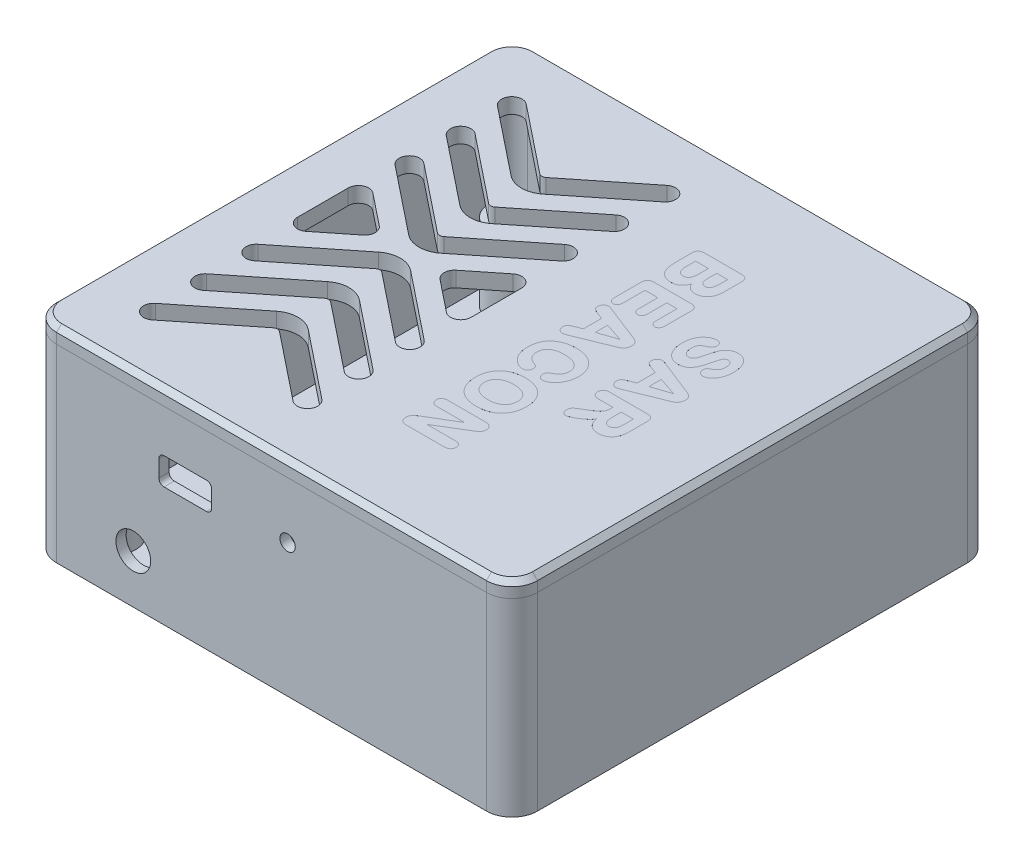
SolidWorks part; units mm, degrees
ref_plane "Front Plane" through (0, 0, 0) normal (0, 0, 1) x (1, 0, 0)
ref_plane "Top Plane" through (0, 0, 0) normal (0, 1, 0) x (1, 0, 0)
ref_plane "Right Plane" through (0, 0, 0) normal (1, 0, 0) x (0, 0, -1)
sketch "Sketch1" plane through (0, 0, 0) normal (0, 1, 0) x (1, 0, 0)
  line L1 (-45, -45) -> (45, -45)
  line L2 (-45, -45) -> (-45, 45)
  line L3 (-45, 45) -> (45, 45)
  line L4 (45, -45) -> (45, 45)
  line L5 (-45, -45) -> (45, 45) construction
  line L6 (-45, 45) -> (45, -45) construction
  point P0 (0, 0)
  dimension "D1" = 90
  dimension "D2" = 90
extrude "Boss-Extrude1" add sketch "Sketch1" along normal blind 35
fillet "Fillet1" radius 3 4 edges at (45, 17.5, 45) (-45, 17.5, 45) (-45, 17.5, -45) (45, 17.5, -45)
shell "Shell1" thickness 2 removed face at (0, 35, 0) outward yes
sketch "Sketch2" plane through (0, 0, 0) normal (0, 1, 0) x (1, 0, 0)
  line L0 (-39, 39) -> (39, 39) construction
  circle A0 centre (-39, 39) radius 2.25
  circle A1 centre (39, 39) radius 2.25
  circle A2 centre (-39, 39) radius 4.5
  circle A3 centre (39, 39) radius 4.5
  point P4 (0, 39)
  dimension "D1" = 4.5
  dimension "D4" = 9
  dimension "D2" = 78
  dimension "D3" = 39
extrude "Boss-Extrude2" add sketch "Sketch2" along normal blind 15
mirror "Mirror1" about plane through (0, 0, 0) normal (0, 0, 1) of "Boss-Extrude2"
sketch "Sketch4" plane through (0, 0, 47) normal (0, 0, 1) x (1, 0, 0)
  line L0 (-42, -2) -> (42, -2) construction
  line L1 (-47, -2) -> (-47, 35) construction
  circle A0 centre (-27, 7.5) radius 3.4
  dimension "D2" = 6.8
  dimension "D1" = 9.5
  dimension "D3" = 20
extrude "Cut-Extrude1" cut sketch "Sketch4" against normal through all
sketch "Sketch5" plane through (0, 0, 47) normal (0, 0, 1) x (1, 0, 0)
  line L1 (-21, 21.35) -> (-12.7, 21.35)
  line L2 (-22, 22.35) -> (-22, 25.65)
  line L3 (-21, 26.65) -> (-12.7, 26.65)
  line L4 (-11.7, 22.35) -> (-11.7, 25.65)
  line L5 (-22, 21.35) -> (-11.7, 26.65) construction
  line L6 (-22, 26.65) -> (-11.7, 21.35) construction
  line L7 (-47, -2) -> (-47, 35) construction
  line L8 (-42, 35) -> (42, 35) construction
  arc A1 (-12.7, 26.65) -> (-11.7, 25.65) centre (-12.7, 25.65) cw
  arc A2 (-12.7, 21.35) -> (-11.7, 22.35) centre (-12.7, 22.35) ccw
  arc A3 (-22, 25.65) -> (-21, 26.65) centre (-21, 25.65) cw
  arc A4 (-21, 21.35) -> (-22, 22.35) centre (-21, 22.35) cw
  point P0 (-16.85, 24)
  point P5 (0, 0)
  point P6 (0, 23.8176)
  point P8 (0, 0)
  point P9 (-27.3536, 23.0928)
  point P10 (-16.7724, 24.9772)
  point P12 (0, 0)
  point P13 (-27.3536, 24.9047)
  dimension "D5" = 1
  dimension "D1" = 10.3
  dimension "D2" = 5.3
  dimension "D3" = 11
  dimension "D4" = 25
extrude "Cut-Extrude2" cut sketch "Sketch5" against normal through all
sketch "Sketch6" plane through (0, 0, 47) normal (0, 0, 1) x (1, 0, 0)
  line L0 (-11.7, 22.35) -> (-11.7, 25.65) construction
  line L1 (-21, 21.35) -> (-12.7, 21.35) construction
  circle A0 centre (3.15, 24) radius 1.5
  point P4 (0, 0)
  point P5 (-11.7, 24)
  point P8 (-16.85, 21.35)
  dimension "D1" = 3
  dimension "D2" = 20
extrude "Cut-Extrude3" cut sketch "Sketch6" against normal up to next
sketch "Sketch7" plane through (-45, 0, 0) normal (1, 0, 0) x (0, 0, -1)
  line L0 (0, 0) -> (0, 15) construction
  line L1 (-37, 26) -> (-27, 26)
  line L2 (-37, 26) -> (-37, 19)
  line L3 (-37, 19) -> (-27, 19)
  line L4 (-27, 26) -> (-27, 19)
  line L5 (-37, 26) -> (-27, 19) construction
  line L6 (-37, 19) -> (-27, 26) construction
  line L7 (42, 0) -> (-42, 0) construction
  line L8 (-42, 0) -> (-42, 35) construction
  point P0 (-32, 22.5)
  dimension "D1" = 15
  dimension "D2" = 11
  dimension "D3" = 7
  dimension "D4" = 15
  dimension "D5" = 10
extrude "Cut-Extrude4" cut sketch "Sketch7" against normal up to next
fillet "Fillet2" radius 1 4 edges at (-46, 19, 27) (-46, 26, 27) (-46, 26, 37) (-46, 19, 37)
sketch "Sketch9" plane through (0, 0, -47) normal (0, 0, -1) x (-1, 0, 0)
  line L0 (22, 25.65) -> (22, 22.35) construction
  line L1 (11.7, 22.35) -> (11.7, 25.65) construction
  line L2 (12.7, 26.65) -> (21, 26.65) construction
  line L3 (21, 21.35) -> (12.7, 21.35) construction
  line L4 (11.7, 22.35) -> (11.7, 25.65) construction
  line L5 (12.7, 26.65) -> (21, 26.65) construction
  line L6 (22, 25.65) -> (22, 22.35) construction
  line L7 (21, 21.35) -> (12.7, 21.35) construction
  line L8 (27, 7.5) -> (35, 7.5) construction
  line L9 (35, 7.5) -> (35, 15.75) construction
  line L10 (22, 24) -> (35, 24) construction
  line L11 (35, 24) -> (35, 15.75) construction
  line L20 (47, 35) -> (47, -2) construction
  circle A0 centre (35, 15.75) radius 2
  arc A1 (11.7, 22.35) -> (12.7, 21.35) centre (12.7, 22.35) ccw construction
  arc A2 (12.7, 26.65) -> (11.7, 25.65) centre (12.7, 25.65) ccw construction
  arc A3 (22, 25.65) -> (21, 26.65) centre (21, 25.65) ccw construction
  arc A4 (21, 21.35) -> (22, 22.35) centre (21, 22.35) ccw construction
  arc A5 (11.7, 22.35) -> (12.7, 21.35) centre (12.7, 22.35) ccw construction
  arc A6 (12.7, 26.65) -> (11.7, 25.65) centre (12.7, 25.65) ccw construction
  arc A7 (22, 25.65) -> (21, 26.65) centre (21, 25.65) ccw construction
  arc A8 (21, 21.35) -> (22, 22.35) centre (21, 22.35) ccw construction
  circle A9 centre (27, 7.5) radius 3.4 construction
  circle A10 centre (27, 7.5) radius 3.4 construction
  dimension "D1" = 4
  dimension "D3" = 12
extrude "Cut-Extrude5" cut sketch "Sketch9" against normal up to next
sketch "Sketch10" plane through (0, 35, 0) normal (0, 1, 0) x (1, 0, 0)
  line L8 (-42, -44.9) -> (42, -44.9)
  line L9 (44.9, -42) -> (44.9, 42)
  line L10 (42, 44.9) -> (-42, 44.9)
  line L11 (-44.9, 42) -> (-44.9, -42)
  line L12 (-42, -44.9) -> (42, -44.9)
  line L13 (44.9, -42) -> (44.9, 42)
  line L14 (42, 44.9) -> (-42, 44.9)
  line L15 (-44.9, 42) -> (-44.9, -42)
  arc A8 (-44.9, -42) -> (-42, -44.9) centre (-42, -42) ccw
  arc A9 (42, -44.9) -> (44.9, -42) centre (42, -42) ccw
  arc A10 (44.9, 42) -> (42, 44.9) centre (42, 42) ccw
  arc A11 (-42, 44.9) -> (-44.9, 42) centre (-42, 42) ccw
  arc A12 (-44.9, -42) -> (-42, -44.9) centre (-42, -42) ccw
  arc A13 (42, -44.9) -> (44.9, -42) centre (42, -42) ccw
  arc A14 (44.9, 42) -> (42, 44.9) centre (42, 42) ccw
  arc A15 (-42, 44.9) -> (-44.9, 42) centre (-42, 42) ccw
  dimension "D1" = 0.1
extrude "Extrude-Thin1" add sketch "Sketch10" against normal blind 4 separate body thin thin type one direction reverse wall 2
sketch "Sketch11" plane through (0, 35, 0) normal (0, 1, 0) x (1, 0, 0)
  line L12 (-42, -47) -> (42, -47)
  line L13 (47, -42) -> (47, 42)
  line L14 (42, 47) -> (-42, 47)
  line L15 (-47, 42) -> (-47, -42)
  line L16 (-42, -47) -> (42, -47)
  line L17 (47, -42) -> (47, 42)
  line L18 (42, 47) -> (-42, 47)
  line L19 (-47, 42) -> (-47, -42)
  arc A12 (42, -47) -> (47, -42) centre (42, -42) ccw
  arc A13 (47, 42) -> (42, 47) centre (42, 42) ccw
  arc A14 (-42, 47) -> (-47, 42) centre (-42, 42) ccw
  arc A15 (-47, -42) -> (-42, -47) centre (-42, -42) ccw
  arc A16 (42, -47) -> (47, -42) centre (42, -42) ccw
  arc A17 (47, 42) -> (42, 47) centre (42, 42) ccw
  arc A18 (-42, 47) -> (-47, 42) centre (-42, 42) ccw
  arc A19 (-47, -42) -> (-42, -47) centre (-42, -42) ccw
  dimension "D1" = 0
extrude "Boss-Extrude4" add sketch "Sketch11" along normal blind 3
chamfer "Chamfer1" distance 1 angle 45 8 edges at (-47, 38, 0) (-45.5355, 38, -45.5355) (0, 38, -47) (45.5355, 38, -45.5355) (47, 38, 0) (45.5355, 38, 45.5355) (0, 38, 47) (-45.5355, 38, 45.5355)
sketch "Sketch12" plane through (0, 38, 0) normal (0, 1, 0) x (1, 0, 0)
  line L0 (22.0361, 46) -> (22.0361, -46) construction
  line L1 (42, 46) -> (-42, 46) construction
  line L2 (-42, -46) -> (42, -46) construction
  line L3 (7.6213, 46) -> (7.6213, -46) construction
  text T0 "<b>SAR </b>" font "Arial Rounded MT Bold" height 10
  text T1 "<b>BEACON</b>" font "Arial Rounded MT Bold" height 10
extrude "Cut-Extrude7" cut sketch "Sketch12" against normal blind 1
sketch "Sketch13" plane through (0, 37, 0) normal (0, 1, 0) x (1, 0, 0)
  line L3 (17.3713, 24.3516) -> (17.3713, 27.4512)
  line L4 (16.0666, 28.75) -> (8.926, 28.75)
  line L5 (7.6213, 27.4512) -> (7.6213, 24.5293)
  line L6 (17.3713, 24.3516) -> (17.3713, 27.4512)
  line L7 (16.0666, 28.75) -> (8.926, 28.75)
  line L8 (7.6213, 27.4512) -> (7.6213, 24.5293)
  line L9 (11.8713, 24.6934) -> (11.8713, 26.5)
  line L10 (11.8713, 26.5) -> (9.3713, 26.5)
  line L11 (9.3713, 26.5) -> (9.3713, 24.627)
  line L12 (11.8713, 24.6934) -> (11.8713, 26.5)
  line L13 (11.8713, 26.5) -> (9.3713, 26.5)
  line L14 (9.3713, 26.5) -> (9.3713, 24.627)
  line L15 (15.6213, 25.1406) -> (15.6213, 26.5)
  line L16 (15.6213, 26.5) -> (13.4963, 26.5)
  line L17 (13.4963, 26.5) -> (13.4963, 24.9395)
  line L18 (15.6213, 25.1406) -> (15.6213, 26.5)
  line L19 (15.6213, 26.5) -> (13.4963, 26.5)
  line L20 (13.4963, 26.5) -> (13.4963, 24.9395)
  line L21 (30.0361, -7.9023) -> (30.0361, -6.3125)
  line L22 (30.0361, -6.3125) -> (27.6611, -6.3125)
  line L23 (9.5529, 1.5586) -> (15.715, 4.0547)
  line L24 (15.6213, 7.6777) -> (9.4982, 10.0898)
  line L25 (8.76, 8.0449) -> (9.8713, 7.625)
  line L26 (9.8713, 7.625) -> (9.8713, 4.0781)
  line L27 (17.3713, 12.5469) -> (17.3713, 17.6016)
  line L28 (16.0666, 18.875) -> (8.926, 18.875)
  line L29 (7.6213, 17.6016) -> (7.6213, 12.3984)
  line L30 (9.3713, 12.3984) -> (9.3713, 16.625)
  line L31 (9.3713, 16.625) -> (11.8713, 16.625)
  line L32 (11.8713, 16.625) -> (11.8713, 12.8906)
  line L33 (13.6213, 12.8906) -> (13.6213, 16.625)
  line L34 (13.6213, 16.625) -> (15.6213, 16.625)
  line L35 (15.6213, 16.625) -> (15.6213, 12.5469)
  line L36 (17.3713, 12.5469) -> (17.3713, 17.6016)
  line L37 (16.0666, 18.875) -> (8.926, 18.875)
  line L38 (7.6213, 17.6016) -> (7.6213, 12.3984)
  line L39 (9.3713, 12.3984) -> (9.3713, 16.625)
  line L40 (9.3713, 16.625) -> (11.8713, 16.625)
  line L41 (11.8713, 16.625) -> (11.8713, 12.8906)
  line L42 (13.6213, 12.8906) -> (13.6213, 16.625)
  line L43 (13.6213, 16.625) -> (15.6213, 16.625)
  line L44 (15.6213, 16.625) -> (15.6213, 12.5469)
  line L45 (9.8713, 4.0781) -> (8.7834, 3.6562)
  line L46 (9.5529, 1.5586) -> (15.715, 4.0547)
  line L47 (15.6213, 7.6777) -> (9.4982, 10.0898)
  line L48 (8.76, 8.0449) -> (9.8713, 7.625)
  line L49 (9.8713, 7.625) -> (9.8713, 4.0781)
  line L50 (9.8713, 4.0781) -> (8.7834, 3.6562)
  line L51 (23.9677, -2.3789) -> (30.1298, 0.1172)
  line L52 (30.0361, 3.7402) -> (23.913, 6.1523)
  line L53 (23.1747, 4.1074) -> (24.2861, 3.6875)
  line L54 (24.2861, 3.6875) -> (24.2861, 0.1406)
  line L55 (24.2861, 0.1406) -> (23.1982, -0.2813)
  line L56 (23.9677, -2.3789) -> (30.1298, 0.1172)
  line L57 (30.0361, 3.7402) -> (23.913, 6.1523)
  line L58 (23.1747, 4.1074) -> (24.2861, 3.6875)
  line L59 (24.2861, 3.6875) -> (24.2861, 0.1406)
  line L60 (24.2861, 0.1406) -> (23.1982, -0.2813)
  line L61 (24.4189, -8.9883) -> (23.165, -9.748)
  line L62 (31.7861, -8.5449) -> (31.7861, -5.3809)
  line L63 (30.4853, -4.0625) -> (23.204, -4.0625)
  line L64 (23.1806, -6.3125) -> (26.0361, -6.3125)
  line L65 (26.0361, -6.3125) -> (26.0361, -6.7598)
  line L66 (24.4189, -8.9883) -> (23.165, -9.748)
  line L67 (31.7861, -8.5449) -> (31.7861, -5.3809)
  line L68 (30.4853, -4.0625) -> (23.204, -4.0625)
  line L69 (23.1806, -6.3125) -> (26.0361, -6.3125)
  line L70 (26.0361, -6.3125) -> (26.0361, -6.7598)
  line L71 (27.6611, -6.3125) -> (27.6611, -7.8477)
  line L72 (30.0361, -7.9023) -> (30.0361, -6.3125)
  line L73 (30.0361, -6.3125) -> (27.6611, -6.3125)
  line L74 (27.6611, -6.3125) -> (27.6611, -7.8477)
  line L75 (11.6213, 4.6289) -> (15.2463, 5.8672)
  line L76 (15.2463, 5.8672) -> (11.6213, 7.0723)
  line L77 (11.6213, 7.0723) -> (11.6213, 4.6289)
  line L78 (11.6213, 4.6289) -> (15.2463, 5.8672)
  line L79 (15.2463, 5.8672) -> (11.6213, 7.0723)
  line L80 (11.6213, 7.0723) -> (11.6213, 4.6289)
  line L81 (26.0361, 0.6914) -> (29.6611, 1.9297)
  line L82 (29.6611, 1.9297) -> (26.0361, 3.1348)
  line L83 (26.0361, 3.1348) -> (26.0361, 0.6914)
  line L84 (15.9885, -21.25) -> (8.715, -21.25)
  line L85 (8.715, -23.375) -> (14.1213, -23.375)
  line L86 (14.1213, -23.375) -> (8.6779, -26.625)
  line L87 (8.8635, -29.5) -> (16.2775, -29.5)
  line L88 (16.2697, -27.375) -> (10.7463, -27.375)
  line L89 (10.7463, -27.375) -> (16.2404, -24.043)
  line L90 (15.9885, -21.25) -> (8.715, -21.25)
  line L91 (8.715, -23.375) -> (14.1213, -23.375)
  line L92 (14.1213, -23.375) -> (8.6779, -26.625)
  line L93 (8.8635, -29.5) -> (16.2775, -29.5)
  line L94 (16.2697, -27.375) -> (10.7463, -27.375)
  line L95 (10.7463, -27.375) -> (16.2404, -24.043)
  line L96 (26.0361, 0.6914) -> (29.6611, 1.9297)
  line L97 (29.6611, 1.9297) -> (26.0361, 3.1348)
  line L98 (26.0361, 3.1348) -> (26.0361, 0.6914)
  spline S2 degree 3 poles (-3989.5453, -58.1224) (38.286, 45.9978) (8.7637, 34.6996) (9.3882, 24.1915) (9.4131, 23.9931) (9.4495, 23.8096) (9.4903, 23.6396) (9.5456, 23.4849) (9.6098, 23.3443) (9.6861, 23.2197) (9.7707, 23.1086) (9.8645, 23.012) (9.9698, 22.9307) (10.0849, 22.8645) (10.2104, 22.8131) (10.3448, 22.7762) (16.0194, 21.928) (24.3821, 59.2678) (-258.3746, -3967.9457) knots -12.026189 -12.026189 -12.026189 -12.026189 0.088138 0.1711 0.249202 0.321151 0.389313 0.452975 0.512444 0.569371 0.622999 0.675099 0.725995 0.777717 0.829484 0.883845 0.939918 7.505211 7.505211 7.505211 7.505211 only from (9.3713, 24.627) to (10.6408, 22.75)
  spline S3 degree 3 poles (294.7649, -3966.9015) (-3.3025, 58.9855) (5.2243, 21.9298) (10.9381, 22.7762) (11.0732, 22.8122) (11.1959, 22.8665) (11.3089, 22.933) (11.4105, 23.0156) (11.5019, 23.1124) (11.5802, 23.2255) (11.6482, 23.3539) (11.7093, 23.4973) (11.7593, 23.6578) (11.7995, 23.8343) (11.8331, 24.0258) (11.8559, 24.2339) (12.4637, 34.1546) (-20.9774, 44.9597) (4010.887, -58.19) knots -6.442029 -6.442029 -6.442029 -6.442029 0.05907 0.114938 0.168383 0.218882 0.268445 0.318361 0.36855 0.420551 0.47568 0.534906 0.599145 0.66816 0.742436 0.822099 0.908136 12.137672 12.137672 12.137672 12.137672 only from (10.6408, 22.75) to (11.8713, 24.6934)
  spline S4 degree 3 poles (9.3713, 24.627) (9.3727, 24.5514) (9.3755, 24.4048) (9.3882, 24.1915) (9.4131, 23.9931) (9.4495, 23.8096) (9.4903, 23.6396) (9.5456, 23.4849) (9.6098, 23.3443) (9.6861, 23.2197) (9.7707, 23.1086) (9.8645, 23.012) (9.9698, 22.9307) (10.0849, 22.8645) (10.2104, 22.8131) (10.3448, 22.7762) (10.4897, 22.7546) (10.5893, 22.7516) (10.6408, 22.75) knots 0 0 0 0 0.088138 0.1711 0.249202 0.321151 0.389313 0.452975 0.512444 0.569371 0.622999 0.675099 0.725995 0.777717 0.829484 0.883845 0.939918 1 1 1 1
  spline S5 degree 3 poles (10.6408, 22.75) (10.6923, 22.7516) (10.7926, 22.7547) (10.9381, 22.7762) (11.0732, 22.8122) (11.1959, 22.8665) (11.3089, 22.933) (11.4105, 23.0156) (11.5019, 23.1124) (11.5802, 23.2255) (11.6482, 23.3539) (11.7093, 23.4973) (11.7593, 23.6578) (11.7995, 23.8343) (11.8331, 24.0258) (11.8559, 24.2339) (11.8697, 24.4581) (11.8707, 24.6133) (11.8713, 24.6934) knots 0 0 0 0 0.05907 0.114938 0.168383 0.218882 0.268445 0.318361 0.36855 0.420551 0.47568 0.534906 0.599145 0.66816 0.742436 0.822099 0.908136 1 1 1 1
  spline S7 degree 3 poles (286.784, -3967.3644) (1.3296, 59.3537) (9.4479, 22.3162) (14.8727, 23.1565) (14.9953, 23.1933) (15.1049, 23.2467) (15.2011, 23.3162) (15.287, 23.3986) (15.3569, 23.4983) (15.4167, 23.6118) (15.4641, 23.7426) (15.5075, 23.8891) (15.5418, 24.0545) (15.5704, 24.2371) (15.5944, 24.4377) (15.6088, 24.6561) (16.1255, 36.7774) (-12.606, 49.5582) (4014.8083, -39.3548) knots -6.239895 -6.239895 -6.239895 -6.239895 0.057186 0.110385 0.159758 0.206409 0.252257 0.298023 0.344934 0.393977 0.447713 0.507224 0.572633 0.645109 0.723307 0.8088 0.901007 14.910472 14.910472 14.910472 14.910472 only from (14.5939, 23.1309) to (15.6213, 25.1406)
  spline S8 degree 3 poles (-3991.754, -22.1006) (40.4903, 55.798) (6.9478, 39.4579) (7.6406, 23.7979) (7.6655, 23.4623) (7.7003, 23.1488) (7.7453, 22.8567) (7.8094, 22.5867) (10.1247, 14.4852) (52.0996, 20.3227) (-3760.272, -1318.9247) knots -18.607822 -18.607822 -18.607822 -18.607822 0.154279 0.299186 0.43564 0.563012 0.682402 0.794468 0.900095 10.907927 10.907927 10.907927 10.907927 only from (7.6213, 24.5293) to (7.9748, 22.1016)
  spline S9 degree 3 poles (-3549.922, -1805.4555) (33.8464, 52.8584) (4.1633, 28.5585) (8.1694, 21.7346) (8.2824, 21.5672) (8.4079, 21.4136) (8.5417, 21.2701) (8.6834, 21.1359) (8.8393, 21.0181) (9.0537, 20.8718) (9.3408, 20.7224) (9.705, 20.5963) (18.9871, 18.564) (34.7859, 77.3977) (-396.5726, -3958.438) knots -7.345671 -7.345671 -7.345671 -7.345671 0.06723 0.132648 0.19657 0.259728 0.321701 0.383675 0.445676 0.507874 0.63124 0.753048 0.874879 9.654759 9.654759 9.654759 9.654759 only from (7.9748, 22.1016) to (10.4748, 20.5)
  spline S10 degree 3 poles (174.5925, -3975.9049) (-8.196, 54.1261) (2.1543, 19.7281) (10.901, 20.5244) (11.1018, 20.5587) (11.2918, 20.6109) (11.4736, 20.6725) (11.6442, 20.7511) (11.8075, 20.8412) (11.9583, 20.9487) (12.1004, 21.0693) (12.234, 21.2023) (12.357, 21.3507) (12.4681, 21.5147) (12.5721, 21.6903) (12.6655, 21.8805) (15.9355, 29.7256) (-17.1409, 50.6132) (3783.3592, -1312.1096) knots -8.013875 -8.013875 -8.013875 -8.013875 0.068275 0.133744 0.197443 0.258623 0.317963 0.376852 0.434131 0.492274 0.549763 0.608348 0.668487 0.729827 0.793456 0.859389 0.927948 8.738719 8.738719 8.738719 8.738719 only from (10.4748, 20.5) to (12.8205, 22.3008)
  spline S11 degree 3 poles (-3503.5065, -1883.7589) (52.7963, 64.4339) (7.9553, 29.3477) (13.1613, 21.7009) (13.3761, 21.4598) (13.6242, 21.268) (13.8955, 21.1134) (14.1963, 21.0069) (22.9976, 19.2329) (37.2884, 74.3886) (-350.6628, -3962.0596) knots -10.131936 -10.131936 -10.131936 -10.131936 0.137236 0.264594 0.386098 0.504117 0.620887 0.740993 0.866748 10.822386 10.822386 10.822386 10.822386 only from (12.8205, 22.3008) to (14.8674, 20.9297)
  spline S12 degree 3 poles (265.3187, -3971.0648) (-1.2723, 60.3255) (8.3625, 20.0196) (15.2658, 20.9605) (15.4607, 21.0012) (15.6518, 21.0595) (15.8376, 21.1365) (16.0175, 21.228) (16.1908, 21.3364) (16.3571, 21.4615) (16.5148, 21.6044) (16.6648, 21.7635) (21.8069, 28.3778) (-5.6922, 57.274) (3329.9852, -2218.7802) knots -8.110179 -8.110179 -8.110179 -8.110179 0.080574 0.160174 0.239282 0.319396 0.399669 0.480425 0.561543 0.644713 0.729949 0.816771 0.906993 10.771624 10.771624 10.771624 10.771624 only from (14.8674, 20.9297) to (16.9279, 22.1348)
  spline S13 degree 3 poles (3586.5687, -1782.265) (-29.9164, 29.4291) (14.3266, 15.6251) (17.1429, 22.5765) (17.2231, 22.8233) (17.2769, 23.0911) (17.3198, 23.3773) (17.3509, 23.6837) (18.0719, 37.442) (-16.8496, 51.9393) (4016.7525, -29.7427) knots -9.481733 -9.481733 -9.481733 -9.481733 0.105014 0.213254 0.32606 0.444721 0.570712 0.705377 0.848088 18.621488 18.621488 18.621488 18.621488 only from (16.9279, 22.1348) to (17.3713, 24.3516)
  spline S14 degree 3 poles (4011.6109, 237.5295) (-18.6894, 13.483) (18.0408, 21.6669) (17.3533, 27.7616) (17.3315, 27.9026) (17.2954, 28.0308) (17.2533, 28.1502) (17.1986, 28.2566) (17.1354, 28.3531) (17.0602, 28.437) (16.9763, 28.5121) (16.8799, 28.5756) (16.7729, 28.6294) (16.6543, 28.6758) (16.5232, 28.7066) (16.3814, 28.7338) (8.4772, 29.3428) (0.1695, 0.9711) (55.0394, 4028.3462) knots -8.426132 -8.426132 -8.426132 -8.426132 0.076222 0.148206 0.214314 0.277119 0.335789 0.39245 0.445412 0.498095 0.550778 0.60374 0.6604 0.719393 0.782852 0.850022 0.922833 11.94326 11.94326 11.94326 11.94326 only from (17.3713, 27.4512) to (16.0666, 28.75)
  spline S15 degree 3 poles (-311.8064, 4015.6184) (29.1154, -23.7111) (16.3712, 30.3143) (8.3528, 28.6848) (8.1228, 28.5891) (7.9633, 28.4757) (7.8629, 28.364) (7.7974, 28.269) (7.7438, 28.1614) (7.698, 28.0425) (7.6638, 27.9114) (7.6379, 27.7685) (7.0177, 20.0337) (36.3795, 11.4603) (-3991.1105, 122.9428) knots -11.075081 -11.075081 -11.075081 -11.075081 0.147169 0.275723 0.390478 0.496241 0.548237 0.60171 0.658367 0.717356 0.781044 0.849113 0.92192 11.708902 11.708902 11.708902 11.708902 only from (8.926, 28.75) to (7.6213, 27.4512)
  spline S16 degree 3 poles (7.6213, 24.5293) (7.6225, 24.4023) (7.6248, 24.1561) (7.6406, 23.7979) (7.6655, 23.4623) (7.7003, 23.1488) (7.7453, 22.8567) (7.8094, 22.5867) (7.8813, 22.3351) (7.9442, 22.1779) (7.9748, 22.1016) knots 0 0 0 0 0.154279 0.299186 0.43564 0.563012 0.682402 0.794468 0.900095 1 1 1 1
  spline S17 degree 3 poles (7.9748, 22.1016) (8.0051, 22.0379) (8.065, 21.9124) (8.1694, 21.7346) (8.2824, 21.5672) (8.4079, 21.4136) (8.5417, 21.2701) (8.6834, 21.1359) (8.8393, 21.0181) (9.0537, 20.8718) (9.3408, 20.7224) (9.705, 20.5963) (10.0844, 20.5133) (10.3435, 20.5045) (10.4748, 20.5) knots 0 0 0 0 0.06723 0.132648 0.19657 0.259728 0.321701 0.383675 0.445676 0.507874 0.63124 0.753048 0.874879 1 1 1 1
  spline S18 degree 3 poles (10.4748, 20.5) (10.5478, 20.5018) (10.6907, 20.5053) (10.901, 20.5244) (11.1018, 20.5587) (11.2918, 20.6109) (11.4736, 20.6725) (11.6442, 20.7511) (11.8075, 20.8412) (11.9583, 20.9487) (12.1004, 21.0693) (12.234, 21.2023) (12.357, 21.3507) (12.4681, 21.5147) (12.5721, 21.6903) (12.6655, 21.8805) (12.7505, 22.0845) (12.7968, 22.2275) (12.8205, 22.3008) knots 0 0 0 0 0.068275 0.133744 0.197443 0.258623 0.317963 0.376852 0.434131 0.492274 0.549763 0.608348 0.668487 0.729827 0.793456 0.859389 0.927948 1 1 1 1
  spline S19 degree 3 poles (12.8205, 22.3008) (12.8716, 22.1918) (12.9702, 21.9816) (13.1613, 21.7009) (13.3761, 21.4598) (13.6242, 21.268) (13.8955, 21.1134) (14.1963, 21.0069) (14.5234, 20.941) (14.7505, 20.9335) (14.8674, 20.9297) knots 0 0 0 0 0.137236 0.264594 0.386098 0.504117 0.620887 0.740993 0.866748 1 1 1 1
  spline S20 degree 3 poles (14.8674, 20.9297) (14.9345, 20.931) (15.068, 20.9336) (15.2658, 20.9605) (15.4607, 21.0012) (15.6518, 21.0595) (15.8376, 21.1365) (16.0175, 21.228) (16.1908, 21.3364) (16.3571, 21.4615) (16.5148, 21.6044) (16.6648, 21.7635) (16.8031, 21.9414) (16.8859, 22.0697) (16.9279, 22.1348) knots 0 0 0 0 0.080574 0.160174 0.239282 0.319396 0.399669 0.480425 0.561543 0.644713 0.729949 0.816771 0.906993 1 1 1 1
  spline S21 degree 3 poles (16.9279, 22.1348) (16.968, 22.2043) (17.0493, 22.3454) (17.1429, 22.5765) (17.2231, 22.8233) (17.2769, 23.0911) (17.3198, 23.3773) (17.3509, 23.6837) (17.3681, 24.0109) (17.3702, 24.2357) (17.3713, 24.3516) knots 0 0 0 0 0.105014 0.213254 0.32606 0.444721 0.570712 0.705377 0.848088 1 1 1 1
  spline S22 degree 3 poles (17.3713, 27.4512) (17.371, 27.5053) (17.3704, 27.6104) (17.3533, 27.7616) (17.3315, 27.9026) (17.2954, 28.0308) (17.2533, 28.1502) (17.1986, 28.2566) (17.1354, 28.3531) (17.0602, 28.437) (16.9763, 28.5121) (16.8799, 28.5756) (16.7729, 28.6294) (16.6543, 28.6758) (16.5232, 28.7066) (16.3814, 28.7338) (16.2276, 28.7456) (16.1213, 28.7485) (16.0666, 28.75) knots 0 0 0 0 0.076222 0.148206 0.214314 0.277119 0.335789 0.39245 0.445412 0.498095 0.550778 0.60374 0.6604 0.719393 0.782852 0.850022 0.922833 1 1 1 1
  spline S23 degree 3 poles (8.926, 28.75) (8.8215, 28.7466) (8.6259, 28.7403) (8.3528, 28.6848) (8.1228, 28.5891) (7.9633, 28.4757) (7.8629, 28.364) (7.7974, 28.269) (7.7438, 28.1614) (7.698, 28.0425) (7.6638, 27.9114) (7.6379, 27.7685) (7.6255, 27.6135) (7.6227, 27.5065) (7.6213, 27.4512) knots 0 0 0 0 0.147169 0.275723 0.390478 0.496241 0.548237 0.60171 0.658367 0.717356 0.781044 0.849113 0.92192 1 1 1 1
  spline S24 degree 3 poles (-3985.3842, -59.5352) (51.237, 49.788) (12.6726, 36.5037) (13.521, 24.3193) (13.5562, 24.0681) (13.6076, 23.8557) (13.6837, 23.6771) (13.7848, 23.5237) (17.5534, 19.666) (52.1571, 55.75) (-2421.5864, -3149.2057) knots -19.468611 -19.468611 -19.468611 -19.468611 0.185245 0.345326 0.484108 0.5995 0.701522 0.799823 0.898418 9.442301 9.442301 9.442301 9.442301 only from (13.4963, 24.9395) to (14.0686, 23.291)
  spline S25 degree 3 poles (-1757.557, -3562.8051) (25.7568, 66.8121) (10.0647, 24.6876) (14.3194, 23.17) (18.6299, 22.0611) (29.0355, 66.2676) (-509.8398, -3942.1458) knots -23.478398 -23.478398 -23.478398 -23.478398 0.254449 0.501939 0.746908 24.114629 24.114629 24.114629 24.114629 only from (14.0686, 23.291) to (14.5939, 23.1309)
  spline S26 degree 3 poles (14.5939, 23.1309) (14.6428, 23.1324) (14.7372, 23.1355) (14.8727, 23.1565) (14.9953, 23.1933) (15.1049, 23.2467) (15.2011, 23.3162) (15.287, 23.3986) (15.3569, 23.4983) (15.4167, 23.6118) (15.4641, 23.7426) (15.5075, 23.8891) (15.5418, 24.0545) (15.5704, 24.2371) (15.5944, 24.4377) (15.6088, 24.6561) (15.6189, 24.8925) (15.6205, 25.056) (15.6213, 25.1406) knots 0 0 0 0 0.057186 0.110385 0.159758 0.206409 0.252257 0.298023 0.344934 0.393977 0.447713 0.507224 0.572633 0.645109 0.723307 0.8088 0.901007 1 1 1 1
  spline S27 degree 3 poles (13.4963, 24.9395) (13.4977, 24.8261) (13.5005, 24.6149) (13.521, 24.3193) (13.5562, 24.0681) (13.6076, 23.8557) (13.6837, 23.6771) (13.7848, 23.5237) (13.9135, 23.3919) (14.0163, 23.325) (14.0686, 23.291) knots 0 0 0 0 0.185245 0.345326 0.484108 0.5995 0.701522 0.799823 0.898418 1 1 1 1
  spline S28 degree 3 poles (14.0686, 23.291) (14.1088, 23.2661) (14.1883, 23.2168) (14.3194, 23.17) (14.4541, 23.1354) (14.5468, 23.1324) (14.5939, 23.1309) knots 0 0 0 0 0.254449 0.501939 0.746908 1 1 1 1
  spline S29 degree 3 poles (476.5037, -3984.5997) (13.3499, 34.2205) (23.9578, -11.0875) (29.2, -9.8941) (29.3547, -9.8387) (29.4958, -9.7551) (29.6228, -9.651) (29.7357, -9.5289) (32.8549, -4.8601) (-4.0556, 20.5927) (3584.8966, -1842.2079) knots -11.620349 -11.620349 -11.620349 -11.620349 0.130179 0.254123 0.375567 0.497213 0.619609 0.742518 0.868802 13.137722 13.137722 13.137722 13.137722 only from (28.8642, -9.9375) to (29.9013, -9.2285)
  spline S30 degree 3 poles (3855.6587, -1175.2432) (-1.9425, -8.7005) (28.9622, -13.3854) (29.9624, -9.0151) (29.9852, -8.8807) (30.0052, -8.7257) (30.017, -8.5496) (30.0301, -8.3524) (30.345, 6.3022) (8.1883, 20.7797) (4029.2351, 55.1989) knots -9.765198 -9.765198 -9.765198 -9.765198 0.073818 0.160867 0.263046 0.379223 0.510926 0.65854 0.822002 33.350182 33.350182 33.350182 33.350182 only from (29.9013, -9.2285) to (30.0361, -7.9023)
  spline S31 degree 3 poles (-3970.9797, -101.944) (64.6748, 17.2444) (26.8352, 3.7988) (27.6868, -8.4813) (27.7214, -8.7591) (27.7681, -9.0082) (27.8341, -9.2273) (27.9182, -9.4174) (28.019, -9.5795) (28.1406, -9.7137) (28.2873, -9.8149) (28.4575, -9.8885) (34.5843, -11.2181) (45.2485, 37.5573) (-318.6257, -3994.4021) knots -13.115751 -13.115751 -13.115751 -13.115751 0.122484 0.23453 0.336432 0.428581 0.511229 0.586116 0.655243 0.719225 0.782622 0.84862 0.92082 7.589978 7.589978 7.589978 7.589978 only from (27.6611, -7.8477) to (28.8642, -9.9375)
  spline S32 degree 3 poles (28.8642, -9.9375) (28.9223, -9.9355) (29.0359, -9.9315) (29.2, -9.8941) (29.3547, -9.8387) (29.4958, -9.7551) (29.6228, -9.651) (29.7357, -9.5289) (29.8305, -9.387) (29.8774, -9.282) (29.9013, -9.2285) knots 0 0 0 0 0.130179 0.254123 0.375567 0.497213 0.619609 0.742518 0.868802 1 1 1 1
  spline S33 degree 3 poles (29.9013, -9.2285) (29.9123, -9.1974) (29.9362, -9.1297) (29.9624, -9.0151) (29.9852, -8.8807) (30.0052, -8.7257) (30.017, -8.5496) (30.0301, -8.3524) (30.0348, -8.1341) (30.0356, -7.9818) (30.0361, -7.9023) knots 0 0 0 0 0.073818 0.160867 0.263046 0.379223 0.510926 0.65854 0.822002 1 1 1 1
  spline S34 degree 3 poles (-3968.7321, -338.8823) (66.9691, 31.5821) (14.1964, 19.3081) (15.6771, 12.0391) (15.7569, 11.8343) (15.873, 11.67) (16.0114, 11.5465) (16.1623, 11.456) (20.7343, 9.9033) (33.7447, 60.9264) (-608.0279, -3939.4565) knots -13.113211 -13.113211 -13.113211 -13.113211 0.170179 0.31802 0.451116 0.571297 0.683982 0.789665 0.892964 9.450087 9.450087 9.450087 9.450087 only from (15.6213, 12.5469) to (16.5002, 11.3906)
  spline S35 degree 3 poles (655.7575, -3936.9493) (-0.7297, 60.5328) (12.3368, 9.9084) (16.8323, 11.4561) (16.9814, 11.5465) (17.1175, 11.6713) (17.2361, 11.8335) (17.3152, 12.0393) (18.7998, 19.286) (-34.0821, 31.793) (4000.0733, -356.6859) knots -8.359807 -8.359807 -8.359807 -8.359807 0.105153 0.207802 0.312956 0.425287 0.546737 0.680467 0.829011 14.144298 14.144298 14.144298 14.144298 only from (16.5002, 11.3906) to (17.3713, 12.5469)
  spline S36 degree 3 poles (4010.4292, 247.9211) (-22.9531, 1.779) (18.2784, 11.1757) (17.342, 17.9869) (17.2995, 18.1582) (17.2392, 18.3136) (17.1612, 18.4523) (17.0626, 18.5724) (16.9409, 18.6682) (16.8015, 18.7456) (16.6436, 18.803) (16.4683, 18.8463) (9.2872, 19.7746) (-0.1127, -21.254) (211.9171, 4013.7951) knots -9.506258 -9.506258 -9.506258 -9.506258 0.096573 0.185544 0.268812 0.347558 0.422367 0.494838 0.56744 0.641793 0.721073 0.806141 0.898791 11.014199 11.014199 11.014199 11.014199 only from (17.3713, 17.6016) to (16.0666, 18.875)
  spline S37 degree 3 poles (-185.5614, 4013.8002) (22.7693, -17.6571) (14.708, 19.5486) (8.6142, 18.8569) (8.473, 18.8344) (8.3425, 18.8023) (8.2242, 18.7579) (8.1152, 18.7086) (8.0199, 18.645) (7.9336, 18.574) (7.8594, 18.4917) (7.7957, 18.3974) (7.7419, 18.2923) (7.6959, 18.1762) (7.6644, 18.0478) (7.6379, 17.9098) (7.0178, 10.405) (36.5788, 2.1827) (-3991.4534, 96.7952) knots -8.498981 -8.498981 -8.498981 -8.498981 0.077851 0.149578 0.217208 0.281253 0.340464 0.39683 0.451054 0.503014 0.555492 0.608175 0.664533 0.723206 0.785456 0.852333 0.923048 11.485461 11.485461 11.485461 11.485461 only from (8.926, 18.875) to (7.6213, 17.6016)
  spline S38 degree 3 poles (-3969.1491, -416.4416) (60.4348, 32.0096) (6.138, 18.8334) (7.6804, 11.8955) (7.7564, 11.6882) (7.8758, 11.5243) (8.0122, 11.3966) (8.1616, 11.3045) (12.4778, 9.7145) (26.2543, 61.4962) (-680.8914, -3928.7847) knots -12.625613 -12.625613 -12.625613 -12.625613 0.168661 0.317517 0.450856 0.573337 0.688231 0.794053 0.895998 9.075853 9.075853 9.075853 9.075853 only from (7.6213, 12.3984) to (8.4904, 11.2363)
  spline S39 degree 3 poles (647.6337, -3937.2055) (-8.8302, 61.2027) (4.3549, 9.7257) (8.8271, 11.3037) (8.9775, 11.3984) (9.1157, 11.5263) (9.2326, 11.6919) (9.3134, 11.8973) (10.8285, 18.9244) (-42.5455, 31.3853) (3991.1873, -366.2022) knots -8.280313 -8.280313 -8.280313 -8.280313 0.10582 0.209474 0.31637 0.430642 0.553437 0.685395 0.833445 13.690748 13.690748 13.690748 13.690748 only from (8.4904, 11.2363) to (9.3713, 12.3984)
  spline S40 degree 3 poles (-3977.5425, -274.6646) (60.4808, 31.3336) (10.4687, 19.9) (11.9272, 12.3916) (12.0123, 12.1926) (12.1283, 12.0327) (12.2699, 11.916) (12.4206, 11.829) (17.0462, 10.3261) (29.4799, 59.1608) (-591.0061, -3942.1687) knots -13.750909 -13.750909 -13.750909 -13.750909 0.169459 0.318583 0.449894 0.570826 0.683916 0.790149 0.894803 9.669111 9.669111 9.669111 9.669111 only from (11.8713, 12.8906) to (12.7521, 11.7656)
  spline S41 degree 3 poles (624.0785, -3941.0268) (-4.0588, 59.434) (8.4865, 10.3243) (13.0821, 11.8289) (13.2314, 11.9174) (13.3668, 12.0401) (13.4856, 12.198) (13.5654, 12.3985) (15.0416, 19.4483) (-37.3558, 31.79) (3995.7953, -362.6397) knots -8.672099 -8.672099 -8.672099 -8.672099 0.105841 0.20997 0.316404 0.429949 0.551621 0.684381 0.832023 14.027028 14.027028 14.027028 14.027028 only from (12.7521, 11.7656) to (13.6213, 12.8906)
  spline S42 degree 3 poles (15.6213, 12.5469) (15.6236, 12.4542) (15.6279, 12.2809) (15.6771, 12.0391) (15.7569, 11.8343) (15.873, 11.67) (16.0114, 11.5465) (16.1623, 11.456) (16.3271, 11.4001) (16.4418, 11.3938) (16.5002, 11.3906) knots 0 0 0 0 0.170179 0.31802 0.451116 0.571297 0.683982 0.789665 0.892964 1 1 1 1
  spline S43 degree 3 poles (16.5002, 11.3906) (16.5573, 11.3939) (16.6701, 11.4003) (16.8323, 11.4561) (16.9814, 11.5465) (17.1175, 11.6713) (17.2361, 11.8335) (17.3152, 12.0393) (17.3647, 12.2808) (17.369, 12.4541) (17.3713, 12.5469) knots 0 0 0 0 0.105153 0.207802 0.312956 0.425287 0.546737 0.680467 0.829011 1 1 1 1
  spline S44 degree 3 poles (17.3713, 17.6016) (17.3701, 17.6694) (17.3678, 17.7996) (17.342, 17.9869) (17.2995, 18.1582) (17.2392, 18.3136) (17.1612, 18.4523) (17.0626, 18.5724) (16.9409, 18.6682) (16.8015, 18.7456) (16.6436, 18.803) (16.4683, 18.8463) (16.2737, 18.8714) (16.1376, 18.8738) (16.0666, 18.875) knots 0 0 0 0 0.096573 0.185544 0.268812 0.347558 0.422367 0.494838 0.56744 0.641793 0.721073 0.806141 0.898791 1 1 1 1
  spline S45 degree 3 poles (8.926, 18.875) (8.8712, 18.8747) (8.7661, 18.8742) (8.6142, 18.8569) (8.473, 18.8344) (8.3425, 18.8023) (8.2242, 18.7579) (8.1152, 18.7086) (8.0199, 18.645) (7.9336, 18.574) (7.8594, 18.4917) (7.7957, 18.3974) (7.7419, 18.2923) (7.6959, 18.1762) (7.6644, 18.0478) (7.6379, 17.9098) (7.6254, 17.7593) (7.6227, 17.6556) (7.6213, 17.6016) knots 0 0 0 0 0.077851 0.149578 0.217208 0.281253 0.340464 0.39683 0.451054 0.503014 0.555492 0.608175 0.664533 0.723206 0.785456 0.852333 0.923048 1 1 1 1
  spline S46 degree 3 poles (7.6213, 12.3984) (7.6233, 12.3069) (7.6272, 12.1347) (7.6804, 11.8955) (7.7564, 11.6882) (7.8758, 11.5243) (8.0122, 11.3966) (8.1616, 11.3045) (8.3221, 11.2454) (8.4339, 11.2394) (8.4904, 11.2363) knots 0 0 0 0 0.168661 0.317517 0.450856 0.573337 0.688231 0.794053 0.895998 1 1 1 1
  spline S47 degree 3 poles (8.4904, 11.2363) (8.5482, 11.2394) (8.6625, 11.2456) (8.8271, 11.3037) (8.9775, 11.3984) (9.1157, 11.5263) (9.2326, 11.6919) (9.3134, 11.8973) (9.3649, 12.1361) (9.3691, 12.3076) (9.3713, 12.3984) knots 0 0 0 0 0.10582 0.209474 0.31637 0.430642 0.553437 0.685395 0.833445 1 1 1 1
  spline S48 degree 3 poles (11.8713, 12.8906) (11.8747, 12.7999) (11.881, 12.6294) (11.9272, 12.3916) (12.0123, 12.1926) (12.1283, 12.0327) (12.2699, 11.916) (12.4206, 11.829) (12.5834, 11.7761) (12.6958, 11.7691) (12.7521, 11.7656) knots 0 0 0 0 0.169459 0.318583 0.449894 0.570826 0.683916 0.790149 0.894803 1 1 1 1
  spline S49 degree 3 poles (12.7521, 11.7656) (12.8085, 11.7691) (12.9203, 11.776) (13.0821, 11.8289) (13.2314, 11.9174) (13.3668, 12.0401) (13.4856, 12.198) (13.5654, 12.3985) (13.6145, 12.633) (13.6189, 12.8011) (13.6213, 12.8906) knots 0 0 0 0 0.105841 0.20997 0.316404 0.429949 0.551621 0.684381 0.832023 1 1 1 1
  spline S50 degree 3 poles (-1535.2393, 3693.2263) (45.5723, -5.4686) (22.3772, 9.6386) (8.3213, 3.4584) (8.1462, 3.3765) (8.0275, 3.3115) (7.9224, 3.2499) (7.8075, 3.166) (7.6866, 3.0465) (7.5968, 2.9041) (7.5439, 2.7764) (7.5179, 2.6703) (6.757, -1.9506) (43.7772, -9.8133) (-3978.4328, 334.5884) knots -23.686997 -23.686997 -23.686997 -23.686997 0.133913 0.287786 0.365788 0.436518 0.499657 0.556566 0.658967 0.763935 0.817909 0.874801 0.934659 8.138023 8.138023 8.138023 8.138023 only from (8.7834, 3.6562) to (7.4963, 2.4336)
  spline S51 degree 3 poles (-3962.7109, -483.5607) (59.8069, 21.7413) (5.8518, 8.3452) (7.5703, 1.9556) (7.6746, 1.7498) (7.8179, 1.575) (7.9816, 1.4367) (8.1484, 1.3281) (12.7127, -0.3503) (26.5419, 49.1824) (-694.8606, -3936.0298) knots -11.119739 -11.119739 -11.119739 -11.119739 0.148227 0.284588 0.418227 0.5509 0.679179 0.793862 0.899602 9.117242 9.117242 9.117242 9.117242 only from (7.4963, 2.4336) to (8.4963, 1.25)
  spline S52 degree 3 poles (392.6434, -3980.1008) (-1.6789, 34.0851) (5.1766, 0.5987) (8.6854, 1.2706) (8.7982, 1.292) (8.9231, 1.3296) (9.0622, 1.3717) (9.214, 1.4247) (20.3434, 5.6925) (23.1375, 30.8115) (1518.0109, -3702.8275) knots -9.392306 -9.392306 -9.392306 -9.392306 0.077776 0.167189 0.271774 0.38917 0.520423 0.666174 0.8249 32.847898 32.847898 32.847898 32.847898 only from (8.4963, 1.25) to (9.5529, 1.5586)
  spline S53 degree 3 poles (1421.7563, -3740.3778) (-13.1149, 18.8272) (5.833, 0.0947) (16.056, 4.186) (16.2063, 4.2438) (16.3892, 4.3169) (16.6103, 4.4228) (16.8243, 4.5533) (16.9926, 4.6812) (17.1073, 4.8033) (17.2158, 4.9403) (17.3136, 5.0967) (17.3965, 5.2722) (17.4549, 5.4689) (18.6281, 12.6481) (-26.4972, 23.3484) (4006.848, -282.1579) knots -11.607529 -11.607529 -11.607529 -11.607529 0.069316 0.132271 0.189917 0.241861 0.343261 0.452253 0.509886 0.569085 0.631184 0.696993 0.766274 0.838434 0.916187 8.535506 8.535506 8.535506 8.535506 only from (15.715, 4.0547) to (17.4963, 5.9141)
  spline S54 degree 3 poles (4006.3592, 295.3383) (-24.8596, -10.0016) (18.5308, -0.1598) (17.4601, 6.3036) (17.4077, 6.4781) (17.3323, 6.6347) (17.2422, 6.7757) (17.14, 6.9009) (17.0282, 7.013) (16.9001, 7.106) (16.7615, 7.193) (16.6087, 7.2749) (16.4404, 7.3523) (16.2625, 7.4261) (16.0858, 7.4962) (15.918, 7.5608) (-13.6037, 19.1841) (-40.7023, 36.6611) (-1566.5994, -3665.065) knots -6.806231 -6.806231 -6.806231 -6.806231 0.072797 0.141533 0.20589 0.267813 0.32755 0.385205 0.441072 0.497006 0.554813 0.616751 0.683065 0.753574 0.823553 0.887304 0.946638 34.896136 34.896136 34.896136 34.896136 only from (17.4963, 5.9141) to (15.6213, 7.6777)
  spline S55 degree 3 poles (-1304.0923, -3767.6651) (46.737, 10.4858) (25.545, 3.6238) (9.1789, 10.2175) (9.0422, 10.2653) (8.8874, 10.3186) (2.8222, 11.8309) (-9.6009, -37.2482) (492.4939, 3980.6556) knots -49.389984 -49.389984 -49.389984 -49.389984 0.174246 0.330388 0.467148 0.583513 0.793268 18.026857 18.026857 18.026857 18.026857 only from (9.4982, 10.0898) to (8.4826, 10.375)
  spline S56 degree 3 poles (-645.7284, 3956.391) (26.903, -40.4901) (12.9513, 11.9689) (8.1105, 10.3015) (7.9402, 10.2025) (7.7888, 10.0661) (7.6607, 9.906) (7.5646, 9.7286) (5.9734, 4.3256) (56.4899, -8.4019) (-3955.0188, 555.1413) knots -9.239092 -9.239092 -9.239092 -9.239092 0.120404 0.238714 0.361544 0.491872 0.622807 0.74875 0.872224 11.202422 11.202422 11.202422 11.202422 only from (8.4826, 10.375) to (7.4963, 9.3359)
  spline S57 degree 3 poles (-3974.5727, -365.2449) (59.1908, 28.173) (5.9672, 15.8238) (7.5589, 8.848) (7.6533, 8.6598) (7.7951, 8.5153) (7.9781, 8.401) (8.1964, 8.2819) (19.5383, 3.1453) (44.8913, 33.3522) (-1439.4304, -3720.2787) knots -10.434416 -10.434416 -10.434416 -10.434416 0.13688 0.253973 0.356631 0.45249 0.557304 0.683472 0.830438 19.45742 19.45742 19.45742 19.45742 only from (7.4963, 9.3359) to (8.76, 8.0449)
  spline S58 degree 3 poles (8.7834, 3.6562) (8.7045, 3.6233) (8.535, 3.5524) (8.3213, 3.4584) (8.1462, 3.3765) (8.0275, 3.3115) (7.9224, 3.2499) (7.8075, 3.166) (7.6866, 3.0465) (7.5968, 2.9041) (7.5439, 2.7764) (7.5179, 2.6703) (7.499, 2.5554) (7.4972, 2.4753) (7.4963, 2.4336) knots 0 0 0 0 0.133913 0.287786 0.365788 0.436518 0.499657 0.556566 0.658967 0.763935 0.817909 0.874801 0.934659 1 1 1 1
  spline S59 degree 3 poles (273.0981, -3984.6497) (3.133, 54.3768) (16.1158, 5.9145) (25.7442, 7.3708) (26.0355, 7.4559) (26.3033, 7.5737) (26.5485, 7.7235) (26.7728, 7.9005) (26.9763, 8.1052) (27.155, 8.3408) (27.3193, 8.599) (27.4675, 8.8828) (27.6037, 9.1887) (27.7265, 9.5187) (27.838, 9.871) (27.9474, 10.2427) (32.7119, 28.2601) (6.4071, 53.764) (3925.2738, -888.4436) knots -5.325719 -5.325719 -5.325719 -5.325719 0.063602 0.123767 0.180324 0.235215 0.289236 0.342871 0.396922 0.452466 0.510243 0.57037 0.633847 0.700103 0.769937 0.843437 0.91984 11.339043 11.339043 11.339043 11.339043 only from (25.0986, 7.3125) to (28.1474, 11.041)
  spline S60 degree 3 poles (-3875.9496, 879.3373) (39.0048, -32.2316) (23.3956, -7.9259) (28.2774, 11.572) (28.3305, 11.7703) (28.3836, 11.9703) (28.4587, 12.1843) (28.5495, 12.384) (28.6368, 12.5343) (28.7086, 12.6363) (28.7871, 12.7249) (28.8721, 12.8008) (28.967, 12.8638) (29.0759, 12.905) (33.1216, 13.9164) (42.6626, -30.0069) (-447.6032, 3983.9915) knots -24.667687 -24.667687 -24.667687 -24.667687 0.127404 0.233408 0.318807 0.382625 0.490646 0.600369 0.654784 0.706439 0.75517 0.801615 0.847863 0.895808 0.945675 6.003638 6.003638 6.003638 6.003638 only from (28.1474, 11.041) to (29.3232, 12.9375)
  spline S61 degree 3 poles (756.3802, 3946.0816) (9.337, -41.0586) (24.9377, 14.7722) (29.7141, 12.8462) (29.8799, 12.716) (30.0241, 12.5417) (30.1428, 12.3288) (30.2259, 12.0798) (31.7439, 3.7397) (-19.531, -9.1255) (4016.8854, 335.1701) knots -7.582534 -7.582534 -7.582534 -7.582534 0.105484 0.20718 0.314478 0.431302 0.558215 0.692526 0.839204 13.737008 13.737008 13.737008 13.737008 only from (29.3232, 12.9375) to (30.2861, 11.5)
  spline S62 degree 3 poles (4027.7916, -125.1141) (-3.4379, 27.3996) (30.8956, 18.6065) (30.2701, 11.146) (30.2494, 10.9868) (30.2206, 10.8403) (30.1814, 10.7078) (30.1353, 10.5874) (30.0785, 10.4813) (29.9906, 10.357) (29.8574, 10.2191) (29.6771, 10.0627) (22.298, 5.1326) (-6.7818, 38.8981) (1969.3567, -3487.8948) knots -10.171634 -10.171634 -10.171634 -10.171634 0.08611 0.166109 0.241084 0.309508 0.373741 0.433144 0.48869 0.540733 0.644612 0.754504 0.872636 12.962039 12.962039 12.962039 12.962039 only from (30.2861, 11.5) to (29.2275, 9.7949)
  spline S63 degree 3 poles (-2056.8369, 3422.5735) (61.7234, -15.2837) (35.0307, 13.8241) (28.9024, 9.593) (28.7717, 9.4946) (28.6638, 9.3935) (28.5787, 9.2801) (28.5217, 9.1444) (27.396, 3.5955) (71.3215, -6.0279) (-3956.0734, 356.9266) knots -16.585883 -16.585883 -16.585883 -16.585883 0.156717 0.297055 0.421181 0.53064 0.633925 0.742571 0.864283 13.503557 13.503557 13.503557 13.503557 only from (29.2275, 9.7949) to (28.4833, 8.8145)
  spline S64 degree 3 poles (-3941.1453, -481.4177) (80.4975, 27.6136) (26.8496, 14.4771) (28.5563, 8.3608) (28.6626, 8.1697) (28.8083, 8.0128) (28.971, 7.8846) (29.1435, 7.7951) (33.5884, 6.1652) (47.9461, 58.1456) (-689.1229, -3926.9568) knots -11.04436 -11.04436 -11.04436 -11.04436 0.146448 0.280838 0.409846 0.540833 0.668454 0.785162 0.893916 9.201129 9.201129 9.201129 9.201129 only from (28.4833, 8.8145) to (29.4931, 7.7227)
  spline S65 degree 3 poles (447.213, -3970.2497) (13.471, 51.7563) (24.1786, 6.5281) (29.8774, 7.7711) (30.075, 7.8343) (30.2765, 7.9218) (30.4784, 8.0402) (30.6788, 8.1895) (30.8729, 8.3736) (31.0668, 8.5835) (31.2509, 8.825) (31.4142, 9.1002) (31.5588, 9.4044) (31.6834, 9.7382) (31.7887, 10.1011) (31.8579, 10.496) (33.2554, 23.0228) (-17.1717, 38.3286) (4027.2534, -176.6127) knots -3.499133 -3.499133 -3.499133 -3.499133 0.039062 0.080078 0.122717 0.168363 0.216771 0.268427 0.323885 0.383383 0.446573 0.512876 0.582627 0.656394 0.734936 0.817934 0.906148 8.588037 8.588037 8.588037 8.588037 only from (29.4931, 7.7227) to (31.9111, 11.3613)
  spline S66 degree 3 poles (4026.3404, 216.1735) (-20.8308, -18.8691) (33.5811, -1.587) (31.8357, 12.4042) (31.734, 12.8798) (31.6108, 13.2496) (31.4917, 13.5248) (31.3953, 13.717) (31.2885, 13.8973) (31.1722, 14.0644) (31.0454, 14.219) (30.9146, 14.3656) (30.7674, 14.4932) (30.6164, 14.6135) (30.4561, 14.7179) (30.291, 14.8111) (30.1193, 14.8895) (29.9402, 14.9511) (29.7574, 15.0028) (29.5678, 15.0383) (21.3731, 15.827) (11.6069, -17.9065) (194.3387, 4011.3175) knots -7.873718 -7.873718 -7.873718 -7.873718 0.105157 0.20417 0.297806 0.38709 0.429921 0.471841 0.511836 0.55147 0.589898 0.627884 0.665362 0.702788 0.739898 0.776279 0.812815 0.849275 0.886138 0.923055 0.96104 5.660167 5.660167 5.660167 5.660167 only from (31.9111, 11.3613) to (29.1728, 15.0625)
  spline S67 degree 3 poles (-165.0971, 4009.8306) (45.5621, -23.569) (36.1077, 15.8769) (28.765, 15.0374) (28.5732, 15.0045) (28.3897, 14.9603) (28.2155, 14.8991) (28.0497, 14.8249) (27.8919, 14.7386) (27.6946, 14.6054) (27.4677, 14.4112) (27.2255, 14.1434) (27.0152, 13.8399) (26.8374, 13.4985) (26.6829, 13.1202) (26.539, 12.7036) (21.8237, -2.9335) (60.6732, -29.9642) (-3851.839, 990.2832) knots -4.475302 -4.475302 -4.475302 -4.475302 0.04345 0.085496 0.12587 0.164757 0.203012 0.240805 0.277866 0.315017 0.389028 0.463461 0.539579 0.618565 0.702995 0.79414 0.893282 10.881123 10.881123 10.881123 10.881123 only from (29.1728, 15.0625) to (26.2841, 11.7598)
  spline S68 degree 3 poles (3941.9533, -803.0832) (8.9597, 54.783) (30.7203, 30.0399) (26.125, 11.077) (26.0463, 10.7921) (25.9736, 10.5436) (25.8928, 10.3272) (25.7995, 10.1369) (25.6919, 9.9686) (25.5688, 9.8247) (25.4296, 9.706) (25.2681, 9.6225) (20.143, 8.118) (7.7496, 59.8932) (554.6713, -3954.7325) knots -20.353065 -20.353065 -20.353065 -20.353065 0.133965 0.252815 0.357442 0.447739 0.527581 0.602382 0.672356 0.739001 0.802804 0.865253 0.930664 6.419606 6.419606 6.419606 6.419606 only from (26.2841, 11.7598) to (24.8954, 9.5625)
  spline S69 degree 3 poles (-353.4019, -3972.2081) (37.4586, 47.4379) (29.1241, 8.6962) (24.6466, 9.5913) (24.5285, 9.6306) (24.4148, 9.6855) (24.3066, 9.7565) (24.2045, 9.844) (24.1066, 9.9456) (24.0154, 10.063) (23.9317, 10.1928) (23.86, 10.3347) (23.7958, 10.4853) (23.749, 10.6478) (23.7093, 10.8192) (23.6795, 11.0004) (23.0174, 19.7316) (54.6804, 29.3854) (-3974.9223, -84.6552) knots -5.418048 -5.418048 -5.418048 -5.418048 0.051949 0.102324 0.152775 0.204151 0.256587 0.310925 0.36847 0.429268 0.492774 0.557349 0.623865 0.693012 0.764222 0.839367 0.917802 11.482022 11.482022 11.482022 11.482022 only from (24.8954, 9.5625) to (23.6611, 11.3906)
  spline S70 degree 3 poles (-3970.4664, 223.1899) (66.9084, -6.9992) (22.6191, 3.7423) (23.6965, 11.8766) (23.7468, 12.0833) (23.8168, 12.2637) (23.9078, 12.4194) (24.0066, 12.5597) (24.1208, 12.6822) (24.253, 12.7883) (24.4045, 12.8864) (24.5802, 12.9845) (34.5443, 17.8275) (57.3999, -6.2265) (-1582.4248, 3675.5777) knots -9.822439 -9.822439 -9.822439 -9.822439 0.107054 0.204429 0.290656 0.369371 0.4425 0.512815 0.581103 0.648563 0.721736 0.803847 0.897015 14.402859 14.402859 14.402859 14.402859 only from (23.6611, 11.3906) to (25.0048, 13.1797)
  spline S71 degree 3 poles (1745.2769, -3597.8581) (-3.9151, 44.4611) (19.7579, 10.0693) (25.3338, 13.3458) (25.4754, 13.454) (25.6018, 13.5768) (25.7079, 13.7189) (25.7858, 13.8836) (27.1249, 19.8853) (-19.8084, 30.4374) (4009.1072, -348.3556) knots -12.782667 -12.782667 -12.782667 -12.782667 0.128404 0.251655 0.372009 0.491302 0.610061 0.731879 0.860119 13.062191 13.062191 13.062191 13.062191 only from (25.0048, 13.1797) to (25.8368, 14.2715)
  spline S72 degree 3 poles (3987.7963, 562.9426) (-25.4193, -3.4654) (27.3611, 9.4384) (25.7711, 14.6594) (25.6793, 14.8276) (25.5535, 14.973) (25.405, 15.0936) (25.2373, 15.1819) (19.9464, 16.6874) (7.8121, -32.9814) (544.1159, 3981.1279) knots -10.18181 -10.18181 -10.18181 -10.18181 0.132889 0.257749 0.379667 0.505181 0.63103 0.751746 0.873451 11.287548 11.287548 11.287548 11.287548 only from (25.8368, 14.2715) to (24.8622, 15.2441)
  spline S73 degree 3 poles (-460.1085, 3985.4144) (47.2553, -39.1618) (32.0593, 17.1431) (24.2088, 15.1458) (23.8788, 15.0128) (23.5515, 14.8325) (23.2381, 14.6128) (22.9531, 14.3576) (16.2949, 6.7553) (54.6376, -33.5152) (-3225.9253, 2347.2818) knots -7.938058 -7.938058 -7.938058 -7.938058 0.110218 0.224614 0.345788 0.475609 0.608322 0.738792 0.868434 10.971014 10.971014 10.971014 10.971014 only from (24.8622, 15.2441) to (22.4931, 13.75)
  spline S74 degree 3 poles (-3523.8562, 1863.5431) (70.8424, 7.4623) (25.6467, 21.1404) (22.2363, 13.2428) (22.1319, 12.9677) (22.0541, 12.6739) (21.9883, 12.3659) (21.945, 12.0413) (20.9363, -0.0293) (61.8041, -13.8672) (-3975.2435, 155.149) knots -9.966061 -9.966061 -9.966061 -9.966061 0.111967 0.226711 0.344162 0.464939 0.591086 0.72206 0.857707 15.122914 15.122914 15.122914 15.122914 only from (22.4931, 13.75) to (21.9111, 11.3516)
  spline S75 degree 3 poles (-3976.0948, -103.4376) (60.5665, 33.875) (21.0953, 21.6203) (21.9364, 10.7468) (21.9692, 10.4581) (22.0128, 10.1793) (22.0747, 9.9118) (22.1458, 9.6537) (22.2322, 9.4066) (22.3318, 9.1707) (22.4422, 8.9466) (22.5645, 8.7376) (22.6919, 8.5403) (22.8349, 8.3614) (22.9817, 8.1914) (23.1433, 8.0402) (23.3109, 7.8999) (23.4896, 7.7773) (23.6747, 7.6685) (23.8641, 7.5722) (24.0585, 7.4914) (24.2581, 7.4275) (24.4617, 7.3766) (24.6697, 7.3388) (33.0013, 6.504) (43.038, 42.3918) (-143.5977, -3988.7672) knots -5.510819 -5.510819 -5.510819 -5.510819 0.053493 0.105417 0.155845 0.204539 0.252086 0.29849 0.343667 0.388115 0.431563 0.473423 0.513981 0.553527 0.592376 0.630685 0.668436 0.705901 0.74323 0.780016 0.816288 0.852577 0.888865 0.925318 0.962402 5.237046 5.237046 5.237046 5.237046 only from (21.9111, 11.3516) to (25.0986, 7.3125)
  spline S76 degree 3 poles (25.0986, 7.3125) (25.2107, 7.3161) (25.4289, 7.3231) (25.7442, 7.3708) (26.0355, 7.4559) (26.3033, 7.5737) (26.5485, 7.7235) (26.7728, 7.9005) (26.9763, 8.1052) (27.155, 8.3408) (27.3193, 8.599) (27.4675, 8.8828) (27.6037, 9.1887) (27.7265, 9.5187) (27.838, 9.871) (27.9474, 10.2427) (28.0511, 10.6349) (28.1148, 10.9035) (28.1474, 11.041) knots 0 0 0 0 0.063602 0.123767 0.180324 0.235215 0.289236 0.342871 0.396922 0.452466 0.510243 0.57037 0.633847 0.700103 0.769937 0.843437 0.91984 1 1 1 1
  spline S77 degree 3 poles (28.1474, 11.041) (28.1713, 11.1407) (28.2151, 11.3232) (28.2774, 11.572) (28.3305, 11.7703) (28.3836, 11.9703) (28.4587, 12.1843) (28.5495, 12.384) (28.6368, 12.5343) (28.7086, 12.6363) (28.7871, 12.7249) (28.8721, 12.8008) (28.967, 12.8638) (29.0759, 12.905) (29.1953, 12.9348) (29.2793, 12.9366) (29.3232, 12.9375) knots 0 0 0 0 0.127404 0.233408 0.318807 0.382625 0.490646 0.600369 0.654784 0.706439 0.75517 0.801615 0.847863 0.895808 0.945675 1 1 1 1
  spline S78 degree 3 poles (29.3232, 12.9375) (29.3909, 12.9326) (29.5239, 12.9229) (29.7141, 12.8462) (29.8799, 12.716) (30.0241, 12.5417) (30.1428, 12.3288) (30.2259, 12.0798) (30.2768, 11.8002) (30.2829, 11.6031) (30.2861, 11.5) knots 0 0 0 0 0.105484 0.20718 0.314478 0.431302 0.558215 0.692526 0.839204 1 1 1 1
  spline S79 degree 3 poles (30.2861, 11.5) (30.2856, 11.4381) (30.2846, 11.3187) (30.2701, 11.146) (30.2494, 10.9868) (30.2206, 10.8403) (30.1814, 10.7078) (30.1353, 10.5874) (30.0785, 10.4813) (29.9906, 10.357) (29.8574, 10.2191) (29.6771, 10.0627) (29.4642, 9.9204) (29.3083, 9.8378) (29.2275, 9.7949) knots 0 0 0 0 0.08611 0.166109 0.241084 0.309508 0.373741 0.433144 0.48869 0.540733 0.644612 0.754504 0.872636 1 1 1 1
  spline S80 degree 3 poles (29.2275, 9.7949) (29.1676, 9.7614) (29.0542, 9.6978) (28.9024, 9.593) (28.7717, 9.4946) (28.6638, 9.3935) (28.5787, 9.2801) (28.5217, 9.1444) (28.4897, 8.9865) (28.4855, 8.8739) (28.4833, 8.8145) knots 0 0 0 0 0.156717 0.297055 0.421181 0.53064 0.633925 0.742571 0.864283 1 1 1 1
  spline S81 degree 3 poles (28.4833, 8.8145) (28.4874, 8.734) (28.4952, 8.5797) (28.5563, 8.3608) (28.6626, 8.1697) (28.8083, 8.0128) (28.971, 7.8846) (29.1435, 7.7951) (29.3162, 7.7318) (29.4346, 7.7257) (29.4931, 7.7227) knots 0 0 0 0 0.146448 0.280838 0.409846 0.540833 0.668454 0.785162 0.893916 1 1 1 1
  spline S82 degree 3 poles (29.4931, 7.7227) (29.5558, 7.7247) (29.6843, 7.7289) (29.8774, 7.7711) (30.075, 7.8343) (30.2765, 7.9218) (30.4784, 8.0402) (30.6788, 8.1895) (30.8729, 8.3736) (31.0668, 8.5835) (31.2509, 8.825) (31.4142, 9.1002) (31.5588, 9.4044) (31.6834, 9.7382) (31.7887, 10.1011) (31.8579, 10.496) (31.9051, 10.9188) (31.909, 11.2108) (31.9111, 11.3613) knots 0 0 0 0 0.039062 0.080078 0.122717 0.168363 0.216771 0.268427 0.323885 0.383383 0.446573 0.512876 0.582627 0.656394 0.734936 0.817934 0.906148 1 1 1 1
  spline S83 degree 3 poles (31.9111, 11.3613) (31.9071, 11.5425) (31.8993, 11.8943) (31.8357, 12.4042) (31.734, 12.8798) (31.6108, 13.2496) (31.4917, 13.5248) (31.3953, 13.717) (31.2885, 13.8973) (31.1722, 14.0644) (31.0454, 14.219) (30.9146, 14.3656) (30.7674, 14.4932) (30.6164, 14.6135) (30.4561, 14.7179) (30.291, 14.8111) (30.1193, 14.8895) (29.9402, 14.9511) (29.7574, 15.0028) (29.5678, 15.0383) (29.3724, 15.0571) (29.2399, 15.0607) (29.1728, 15.0625) knots 0 0 0 0 0.105157 0.20417 0.297806 0.38709 0.429921 0.471841 0.511836 0.55147 0.589898 0.627884 0.665362 0.702788 0.739898 0.776279 0.812815 0.849275 0.886138 0.923055 0.96104 1 1 1 1
  spline S84 degree 3 poles (29.1728, 15.0625) (29.103, 15.0618) (28.9658, 15.0603) (28.765, 15.0374) (28.5732, 15.0045) (28.3897, 14.9603) (28.2155, 14.8991) (28.0497, 14.8249) (27.8919, 14.7386) (27.6946, 14.6054) (27.4677, 14.4112) (27.2255, 14.1434) (27.0152, 13.8399) (26.8374, 13.4985) (26.6829, 13.1202) (26.539, 12.7036) (26.4014, 12.2473) (26.3241, 11.9262) (26.2841, 11.7598) knots 0 0 0 0 0.04345 0.085496 0.12587 0.164757 0.203012 0.240805 0.277866 0.315017 0.389028 0.463461 0.539579 0.618565 0.702995 0.79414 0.893282 1 1 1 1
  spline S85 degree 3 poles (26.2841, 11.7598) (26.2565, 11.6366) (26.2043, 11.4043) (26.125, 11.077) (26.0463, 10.7921) (25.9736, 10.5436) (25.8928, 10.3272) (25.7995, 10.1369) (25.6919, 9.9686) (25.5688, 9.8247) (25.4296, 9.706) (25.2681, 9.6225) (25.0882, 9.5697) (24.9609, 9.5649) (24.8954, 9.5625) knots 0 0 0 0 0.133965 0.252815 0.357442 0.447739 0.527581 0.602382 0.672356 0.739001 0.802804 0.865253 0.930664 1 1 1 1
  spline S86 degree 3 poles (24.8954, 9.5625) (24.853, 9.5639) (24.7694, 9.5668) (24.6466, 9.5913) (24.5285, 9.6306) (24.4148, 9.6855) (24.3066, 9.7565) (24.2045, 9.844) (24.1066, 9.9456) (24.0154, 10.063) (23.9317, 10.1928) (23.86, 10.3347) (23.7958, 10.4853) (23.749, 10.6478) (23.7093, 10.8192) (23.6795, 11.0004) (23.6649, 11.1925) (23.6624, 11.3235) (23.6611, 11.3906) knots 0 0 0 0 0.051949 0.102324 0.152775 0.204151 0.256587 0.310925 0.36847 0.429268 0.492774 0.557349 0.623865 0.693012 0.764222 0.839367 0.917802 1 1 1 1
  spline S87 degree 3 poles (23.6611, 11.3906) (23.6626, 11.4773) (23.6655, 11.6429) (23.6965, 11.8766) (23.7468, 12.0833) (23.8168, 12.2637) (23.9078, 12.4194) (24.0066, 12.5597) (24.1208, 12.6822) (24.253, 12.7883) (24.4045, 12.8864) (24.5802, 12.9845) (24.7828, 13.083) (24.9284, 13.1464) (25.0048, 13.1797) knots 0 0 0 0 0.107054 0.204429 0.290656 0.369371 0.4425 0.512815 0.581103 0.648563 0.721736 0.803847 0.897015 1 1 1 1
  spline S88 degree 3 poles (25.0048, 13.1797) (25.0627, 13.2045) (25.1761, 13.2532) (25.3338, 13.3458) (25.4754, 13.454) (25.6018, 13.5768) (25.7079, 13.7189) (25.7858, 13.8836) (25.8277, 14.0715) (25.8337, 14.2029) (25.8368, 14.2715) knots 0 0 0 0 0.128404 0.251655 0.372009 0.491302 0.610061 0.731879 0.860119 1 1 1 1
  spline S89 degree 3 poles (25.8368, 14.2715) (25.8339, 14.3396) (25.8282, 14.4717) (25.7711, 14.6594) (25.6793, 14.8276) (25.5535, 14.973) (25.405, 15.0936) (25.2373, 15.1819) (25.0541, 15.2341) (24.927, 15.2407) (24.8622, 15.2441) knots 0 0 0 0 0.132889 0.257749 0.379667 0.505181 0.63103 0.751746 0.873451 1 1 1 1
  spline S90 degree 3 poles (24.8622, 15.2441) (24.755, 15.2392) (24.5365, 15.2292) (24.2088, 15.1458) (23.8788, 15.0128) (23.5515, 14.8325) (23.2381, 14.6128) (22.9531, 14.3576) (22.7014, 14.0703) (22.5629, 13.8573) (22.4931, 13.75) knots 0 0 0 0 0.110218 0.224614 0.345788 0.475609 0.608322 0.738792 0.868434 1 1 1 1
  spline S91 degree 3 poles (22.4931, 13.75) (22.4458, 13.6695) (22.3502, 13.5065) (22.2363, 13.2428) (22.1319, 12.9677) (22.0541, 12.6739) (21.9883, 12.3659) (21.945, 12.0413) (21.9166, 11.7017) (21.913, 11.4701) (21.9111, 11.3516) knots 0 0 0 0 0.111967 0.226711 0.344162 0.464939 0.591086 0.72206 0.857707 1 1 1 1
  spline S92 degree 3 poles (21.9111, 11.3516) (21.9118, 11.2487) (21.9132, 11.0459) (21.9364, 10.7468) (21.9692, 10.4581) (22.0128, 10.1793) (22.0747, 9.9118) (22.1458, 9.6537) (22.2322, 9.4066) (22.3318, 9.1707) (22.4422, 8.9466) (22.5645, 8.7376) (22.6919, 8.5403) (22.8349, 8.3614) (22.9817, 8.1914) (23.1433, 8.0402) (23.3109, 7.8999) (23.4896, 7.7773) (23.6747, 7.6685) (23.8641, 7.5722) (24.0585, 7.4914) (24.2581, 7.4275) (24.4617, 7.3766) (24.6697, 7.3388) (24.8826, 7.3175) (25.0262, 7.3142) (25.0986, 7.3125) knots 0 0 0 0 0.053493 0.105417 0.155845 0.204539 0.252086 0.29849 0.343667 0.388115 0.431563 0.473423 0.513981 0.553527 0.592376 0.630685 0.668436 0.705901 0.74323 0.780016 0.816288 0.852577 0.888865 0.925318 0.962402 1 1 1 1
  spline S93 degree 3 poles (7.4963, 2.4336) (7.5003, 2.3492) (7.508, 2.1872) (7.5703, 1.9556) (7.6746, 1.7498) (7.8179, 1.575) (7.9816, 1.4367) (8.1484, 1.3281) (8.322, 1.2643) (8.4392, 1.2547) (8.4963, 1.25) knots 0 0 0 0 0.148227 0.284588 0.418227 0.5509 0.679179 0.793862 0.899602 1 1 1 1
  spline S94 degree 3 poles (8.4963, 1.25) (8.525, 1.2505) (8.5867, 1.2517) (8.6854, 1.2706) (8.7982, 1.292) (8.9231, 1.3296) (9.0622, 1.3717) (9.214, 1.4247) (9.3791, 1.488) (9.4931, 1.5343) (9.5529, 1.5586) knots 0 0 0 0 0.077776 0.167189 0.271774 0.38917 0.520423 0.666174 0.8249 1 1 1 1
  spline S95 degree 3 poles (15.715, 4.0547) (15.7757, 4.0772) (15.8914, 4.1202) (16.056, 4.186) (16.2063, 4.2438) (16.3892, 4.3169) (16.6103, 4.4228) (16.8243, 4.5533) (16.9926, 4.6812) (17.1073, 4.8033) (17.2158, 4.9403) (17.3136, 5.0967) (17.3965, 5.2722) (17.4549, 5.4689) (17.4902, 5.6849) (17.4942, 5.8358) (17.4963, 5.9141) knots 0 0 0 0 0.069316 0.132271 0.189917 0.241861 0.343261 0.452253 0.509886 0.569085 0.631184 0.696993 0.766274 0.838434 0.916187 1 1 1 1
  spline S96 degree 3 poles (17.4963, 5.9141) (17.4947, 5.9819) (17.4915, 6.1138) (17.4601, 6.3036) (17.4077, 6.4781) (17.3323, 6.6347) (17.2422, 6.7757) (17.14, 6.9009) (17.0282, 7.013) (16.9001, 7.106) (16.7615, 7.193) (16.6087, 7.2749) (16.4404, 7.3523) (16.2625, 7.4261) (16.0858, 7.4962) (15.918, 7.5608) (15.7651, 7.621) (15.6675, 7.6595) (15.6213, 7.6777) knots 0 0 0 0 0.072797 0.141533 0.20589 0.267813 0.32755 0.385205 0.441072 0.497006 0.554813 0.616751 0.683065 0.753574 0.823553 0.887304 0.946638 1 1 1 1
  spline S97 degree 3 poles (9.4982, 10.0898) (9.4409, 10.1126) (9.3323, 10.1557) (9.1789, 10.2175) (9.0422, 10.2653) (8.8874, 10.3186) (8.7033, 10.3645) (8.5558, 10.3715) (8.4826, 10.375) knots 0 0 0 0 0.174246 0.330388 0.467148 0.583513 0.793268 1 1 1 1
  spline S98 degree 3 poles (8.4826, 10.375) (8.419, 10.3714) (8.2928, 10.3643) (8.1105, 10.3015) (7.9402, 10.2025) (7.7888, 10.0661) (7.6607, 9.906) (7.5646, 9.7286) (7.5079, 9.5359) (7.5002, 9.4034) (7.4963, 9.3359) knots 0 0 0 0 0.120404 0.238714 0.361544 0.491872 0.622807 0.74875 0.872224 1 1 1 1
  spline S99 degree 3 poles (7.4963, 9.3359) (7.4998, 9.2458) (7.5063, 9.0785) (7.5589, 8.848) (7.6533, 8.6598) (7.7951, 8.5153) (7.9781, 8.401) (8.1964, 8.2819) (8.4621, 8.1616) (8.6561, 8.0856) (8.76, 8.0449) knots 0 0 0 0 0.13688 0.253973 0.356631 0.45249 0.557304 0.683472 0.830438 1 1 1 1
  spline S100 degree 3 poles (-1520.8246, 3689.2888) (59.9871, -9.4061) (36.792, 5.7011) (22.736, -0.4791) (22.561, -0.561) (22.4423, -0.626) (22.3372, -0.6876) (22.2223, -0.7715) (22.1014, -0.891) (22.0116, -1.0334) (21.9587, -1.1611) (21.9327, -1.2672) (21.1718, -5.8881) (58.192, -13.7508) (-3964.0181, 330.6509) knots -23.686997 -23.686997 -23.686997 -23.686997 0.133913 0.287786 0.365788 0.436518 0.499657 0.556566 0.658967 0.763935 0.817909 0.874801 0.934659 8.138023 8.138023 8.138023 8.138023 only from (23.1982, -0.2813) to (21.9111, -1.5039)
  spline S101 degree 3 poles (-3948.2961, -487.4982) (74.2217, 17.8038) (20.2665, 4.4077) (21.9851, -1.9819) (22.0894, -2.1877) (22.2327, -2.3625) (22.3964, -2.5008) (22.5632, -2.6094) (27.1275, -4.2878) (40.9567, 45.2449) (-680.4458, -3939.9673) knots -11.119739 -11.119739 -11.119739 -11.119739 0.148227 0.284588 0.418227 0.5509 0.679179 0.793862 0.899602 9.117242 9.117242 9.117242 9.117242 only from (21.9111, -1.5039) to (22.9111, -2.6875)
  spline S102 degree 3 poles (407.0581, -3984.0383) (12.7359, 30.1476) (19.5913, -3.3388) (23.1002, -2.6669) (23.213, -2.6455) (23.3379, -2.6079) (23.477, -2.5658) (23.6287, -2.5128) (34.7581, 1.755) (37.5523, 26.874) (1532.4257, -3706.765) knots -9.392306 -9.392306 -9.392306 -9.392306 0.077776 0.167189 0.271774 0.38917 0.520423 0.666174 0.8249 32.847898 32.847898 32.847898 32.847898 only from (22.9111, -2.6875) to (23.9677, -2.3789)
  spline S103 degree 3 poles (1436.1711, -3744.3153) (1.2998, 14.8897) (20.2478, -3.8428) (30.4708, 0.2485) (30.6211, 0.3063) (30.804, 0.3794) (31.0251, 0.4853) (31.2391, 0.6158) (31.4074, 0.7437) (31.5221, 0.8658) (31.6306, 1.0028) (31.7283, 1.1592) (31.8113, 1.3347) (31.8697, 1.5314) (33.0429, 8.7106) (-12.0824, 19.4109) (4021.2628, -286.0954) knots -11.607529 -11.607529 -11.607529 -11.607529 0.069316 0.132271 0.189917 0.241861 0.343261 0.452253 0.509886 0.569085 0.631184 0.696993 0.766274 0.838434 0.916187 8.535506 8.535506 8.535506 8.535506 only from (30.1298, 0.1172) to (31.9111, 1.9766)
  spline S104 degree 3 poles (4020.774, 291.4008) (-10.4448, -13.9391) (32.9456, -4.0973) (31.8748, 2.3661) (31.8225, 2.5406) (31.747, 2.6972) (31.6569, 2.8382) (31.5548, 2.9634) (31.443, 3.0755) (31.3149, 3.1685) (31.1763, 3.2555) (31.0234, 3.3374) (30.8552, 3.4148) (30.6773, 3.4886) (30.5006, 3.5587) (30.3328, 3.6233) (0.8111, 15.2466) (-26.2875, 32.7236) (-1552.1846, -3669.0025) knots -6.806231 -6.806231 -6.806231 -6.806231 0.072797 0.141533 0.20589 0.267813 0.32755 0.385205 0.441072 0.497006 0.554813 0.616751 0.683065 0.753574 0.823553 0.887304 0.946638 34.896136 34.896136 34.896136 34.896136 only from (31.9111, 1.9766) to (30.0361, 3.7402)
  spline S105 degree 3 poles (-1289.6776, -3771.6026) (61.1518, 6.5483) (39.9598, -0.3137) (23.5937, 6.28) (23.457, 6.3278) (23.3022, 6.3811) (17.237, 7.8934) (4.8138, -41.1857) (506.9087, 3976.7181) knots -49.389984 -49.389984 -49.389984 -49.389984 0.174246 0.330388 0.467148 0.583513 0.793268 18.026857 18.026857 18.026857 18.026857 only from (23.913, 6.1523) to (22.8974, 6.4375)
  spline S106 degree 3 poles (-631.3136, 3952.4535) (41.3178, -44.4276) (27.366, 8.0314) (22.5253, 6.364) (22.355, 6.265) (22.2036, 6.1286) (22.0754, 5.9685) (21.9794, 5.7911) (20.3881, 0.3881) (70.9047, -12.3394) (-3940.604, 551.2038) knots -9.239092 -9.239092 -9.239092 -9.239092 0.120404 0.238714 0.361544 0.491872 0.622807 0.74875 0.872224 11.202422 11.202422 11.202422 11.202422 only from (22.8974, 6.4375) to (21.9111, 5.3984)
  spline S107 degree 3 poles (-3960.1579, -369.1824) (73.6056, 24.2355) (20.382, 11.8863) (21.9737, 4.9105) (22.0681, 4.7223) (22.2098, 4.5778) (22.3929, 4.4635) (22.6112, 4.3444) (33.9531, -0.7922) (59.306, 29.4147) (-1425.0156, -3724.2162) knots -10.434416 -10.434416 -10.434416 -10.434416 0.13688 0.253973 0.356631 0.45249 0.557304 0.683472 0.830438 19.45742 19.45742 19.45742 19.45742 only from (21.9111, 5.3984) to (23.1747, 4.1074)
  spline S108 degree 3 poles (23.1982, -0.2813) (23.1193, -0.3142) (22.9498, -0.3851) (22.736, -0.4791) (22.561, -0.561) (22.4423, -0.626) (22.3372, -0.6876) (22.2223, -0.7715) (22.1014, -0.891) (22.0116, -1.0334) (21.9587, -1.1611) (21.9327, -1.2672) (21.9138, -1.3821) (21.912, -1.4622) (21.9111, -1.5039) knots 0 0 0 0 0.133913 0.287786 0.365788 0.436518 0.499657 0.556566 0.658967 0.763935 0.817909 0.874801 0.934659 1 1 1 1
  spline S109 degree 3 poles (21.9111, -1.5039) (21.9151, -1.5883) (21.9228, -1.7503) (21.9851, -1.9819) (22.0894, -2.1877) (22.2327, -2.3625) (22.3964, -2.5008) (22.5632, -2.6094) (22.7367, -2.6732) (22.854, -2.6828) (22.9111, -2.6875) knots 0 0 0 0 0.148227 0.284588 0.418227 0.5509 0.679179 0.793862 0.899602 1 1 1 1
  spline S110 degree 3 poles (22.9111, -2.6875) (22.9398, -2.687) (23.0015, -2.6858) (23.1002, -2.6669) (23.213, -2.6455) (23.3379, -2.6079) (23.477, -2.5658) (23.6287, -2.5128) (23.7938, -2.4495) (23.9079, -2.4032) (23.9677, -2.3789) knots 0 0 0 0 0.077776 0.167189 0.271774 0.38917 0.520423 0.666174 0.8249 1 1 1 1
  spline S111 degree 3 poles (30.1298, 0.1172) (30.1905, 0.1397) (30.3062, 0.1827) (30.4708, 0.2485) (30.6211, 0.3063) (30.804, 0.3794) (31.0251, 0.4853) (31.2391, 0.6158) (31.4074, 0.7437) (31.5221, 0.8658) (31.6306, 1.0028) (31.7283, 1.1592) (31.8113, 1.3347) (31.8697, 1.5314) (31.905, 1.7474) (31.909, 1.8983) (31.9111, 1.9766) knots 0 0 0 0 0.069316 0.132271 0.189917 0.241861 0.343261 0.452253 0.509886 0.569085 0.631184 0.696993 0.766274 0.838434 0.916187 1 1 1 1
  spline S112 degree 3 poles (31.9111, 1.9766) (31.9094, 2.0444) (31.9063, 2.1763) (31.8748, 2.3661) (31.8225, 2.5406) (31.747, 2.6972) (31.6569, 2.8382) (31.5548, 2.9634) (31.443, 3.0755) (31.3149, 3.1685) (31.1763, 3.2555) (31.0234, 3.3374) (30.8552, 3.4148) (30.6773, 3.4886) (30.5006, 3.5587) (30.3328, 3.6233) (30.1799, 3.6835) (30.0823, 3.722) (30.0361, 3.7402) knots 0 0 0 0 0.072797 0.141533 0.20589 0.267813 0.32755 0.385205 0.441072 0.497006 0.554813 0.616751 0.683065 0.753574 0.823553 0.887304 0.946638 1 1 1 1
  spline S113 degree 3 poles (23.913, 6.1523) (23.8557, 6.1751) (23.747, 6.2182) (23.5937, 6.28) (23.457, 6.3278) (23.3022, 6.3811) (23.1181, 6.427) (22.9706, 6.434) (22.8974, 6.4375) knots 0 0 0 0 0.174246 0.330388 0.467148 0.583513 0.793268 1 1 1 1
  spline S114 degree 3 poles (22.8974, 6.4375) (22.8337, 6.4339) (22.7076, 6.4268) (22.5253, 6.364) (22.355, 6.265) (22.2036, 6.1286) (22.0754, 5.9685) (21.9794, 5.7911) (21.9227, 5.5984) (21.915, 5.4659) (21.9111, 5.3984) knots 0 0 0 0 0.120404 0.238714 0.361544 0.491872 0.622807 0.74875 0.872224 1 1 1 1
  spline S115 degree 3 poles (21.9111, 5.3984) (21.9146, 5.3083) (21.9211, 5.141) (21.9737, 4.9105) (22.0681, 4.7223) (22.2098, 4.5778) (22.3929, 4.4635) (22.6112, 4.3444) (22.8769, 4.2241) (23.0708, 4.1481) (23.1747, 4.1074) knots 0 0 0 0 0.13688 0.253973 0.356631 0.45249 0.557304 0.683472 0.830438 1 1 1 1
  spline S116 degree 3 poles (27.6611, -7.8477) (27.6626, -7.9597) (27.6655, -8.1742) (27.6868, -8.4813) (27.7214, -8.7591) (27.7681, -9.0082) (27.8341, -9.2273) (27.9182, -9.4174) (28.019, -9.5795) (28.1406, -9.7137) (28.2873, -9.8149) (28.4575, -9.8885) (28.6531, -9.9309) (28.7917, -9.9352) (28.8642, -9.9375) knots 0 0 0 0 0.122484 0.23453 0.336432 0.428581 0.511229 0.586116 0.655243 0.719225 0.782622 0.84862 0.92082 1 1 1 1
  spline S118 degree 3 poles (4022.0273, -179.3515) (-12.9869, 11.5298) (26.9054, 1.1842) (26.0087, -7.2149) (25.9706, -7.4126) (25.9156, -7.5925) (25.836, -7.7592) (25.7335, -7.9232) (25.6007, -8.0848) (25.4395, -8.2496) (25.2424, -8.4185) (25.0063, -8.5981) (12.9392, -16.9914) (-19.1374, 5.2849) (2182.7561, -3376.3072) knots -8.432939 -8.432939 -8.432939 -8.432939 0.082932 0.158227 0.227052 0.28942 0.350721 0.416193 0.487495 0.565019 0.652679 0.753755 0.869468 15.739799 15.739799 15.739799 15.739799 only from (26.0361, -6.7598) to (24.4189, -8.9883)
  spline S119 degree 3 poles (2214.6724, -3355.6005) (38.4958, 24.3285) (36.3936, -1.787) (22.779, -9.984) (22.6229, -10.0889) (22.4441, -10.2026) (22.2535, -10.3593) (22.0983, -10.5469) (22.0004, -10.7182) (21.9473, -10.8632) (20.8753, -16.2887) (64.4231, -25.6765) (-3962.9541, 331.1381) knots -23.274729 -23.274729 -23.274729 -23.274729 0.121557 0.228355 0.321949 0.400792 0.542913 0.686527 0.759686 0.834943 0.914775 8.93207 8.93207 8.93207 8.93207 only from (23.165, -9.748) to (21.9111, -11.1914)
  spline S120 degree 3 poles (-3959.6286, -392.8096) (65.1821, 3.7424) (20.9167, -6.1261) (21.9445, -11.5241) (21.9819, -11.6773) (22.0449, -11.8154) (22.1155, -11.9407) (22.1994, -12.0494) (22.2901, -12.1439) (22.3908, -12.2195) (22.492, -12.2803) (22.5941, -12.3207) (25.7129, -13.312) (35.5979, 27.5869) (-609.0501, -3961.9552) knots -9.926952 -9.926952 -9.926952 -9.926952 0.108293 0.209409 0.307598 0.401769 0.491629 0.575748 0.657407 0.735448 0.810083 0.877126 0.94024 6.873637 6.873637 6.873637 6.873637 only from (21.9111, -11.1914) to (22.79, -12.3555)
  spline S121 degree 3 poles (678.4451, -3958.0674) (8.8725, 23.5062) (19.1547, -13.4531) (23.0542, -12.3036) (23.2335, -12.2404) (23.4473, -12.156) (23.6874, -12.0464) (23.9481, -11.9168) (24.2237, -11.7617) (24.5156, -11.5938) (24.8106, -11.406) (25.1016, -11.2061) (25.3818, -10.9915) (25.6494, -10.77) (25.8919, -10.5434) (26.0902, -10.3129) (29.9149, -4.7112) (-14.2976, 25.5458) (3590.2277, -1825.6711) knots -2.616978 -2.616978 -2.616978 -2.616978 0.0242 0.057195 0.099801 0.152028 0.211541 0.277072 0.347554 0.424 0.50324 0.582469 0.661118 0.740307 0.815798 0.883737 0.944396 5.345195 5.345195 5.345195 5.345195 only from (22.79, -12.3555) to (26.3427, -9.8477)
  spline S122 degree 3 poles (-3861.0976, -951.1722) (59.4352, 18.0286) (23.6454, -0.9482) (26.4773, -10.3662) (26.5672, -10.6048) (26.673, -10.8282) (26.7933, -11.037) (26.9297, -11.2296) (27.0779, -11.4086) (27.2421, -11.5709) (27.4206, -11.7152) (27.61, -11.8442) (27.8151, -11.9484) (28.0299, -12.038) (28.259, -12.1033) (28.4992, -12.1523) (37.286, -13.1882) (48.3704, 28.7287) (-166.519, -4007.0413) knots -7.362231 -7.362231 -7.362231 -7.362231 0.070534 0.138579 0.203478 0.26672 0.328719 0.388808 0.448249 0.507453 0.566256 0.624796 0.683546 0.743131 0.803734 0.866661 0.93177 7.605143 7.605143 7.605143 7.605143 only from (26.3427, -9.8477) to (29.0146, -12.1875)
  spline S123 degree 3 poles (244.9519, -4006.0268) (9.4765, 27.5846) (20.7277, -13.2346) (29.527, -12.1485) (29.7746, -12.0935) (30.0164, -12.0176) (30.2483, -11.9176) (30.4706, -11.7971) (30.6781, -11.6499) (30.8765, -11.485) (31.0577, -11.2955) (31.22, -11.0846) (35.7483, -4.0304) (-2.1779, 25.8227) (3563.191, -1887.9564) knots -8.285417 -8.285417 -8.285417 -8.285417 0.083565 0.165155 0.246783 0.327775 0.409038 0.489939 0.571081 0.653938 0.738284 0.823282 0.910175 8.800521 8.800521 8.800521 8.800521 only from (29.0146, -12.1875) to (31.4853, -10.6055)
  spline S124 degree 3 poles (3750.4689, -1482.6089) (-10.5385, -9.5138) (29.4429, -17.2591) (31.6364, -10.1972) (31.6853, -9.9667) (31.7252, -9.7191) (31.7502, -9.4521) (31.7729, -9.167) (32.3095, 5.7637) (2.4479, 20.9258) (4031.4326, -7.7289) knots -10.233705 -10.233705 -10.233705 -10.233705 0.099767 0.205186 0.317687 0.436469 0.563762 0.701011 0.845433 21.923282 21.923282 21.923282 21.923282 only from (31.4853, -10.6055) to (31.7861, -8.5449)
  spline S125 degree 3 poles (4030.6666, 80.8522) (3.0537, -21.1369) (32.3891, -12.7186) (31.7694, -5.0668) (31.7433, -4.9254) (31.7111, -4.794) (31.6655, -4.6746) (31.6116, -4.5657) (31.5481, -4.4674) (31.4738, -4.3813) (31.3877, -4.3061) (31.2926, -4.2395) (31.1848, -4.1841) (31.0659, -4.14) (30.9364, -4.1051) (30.7961, -4.079) (23.1199, -3.4634) (14.6469, -32.3327) (122.3075, 3994.652) knots -10.545864 -10.545864 -10.545864 -10.545864 0.076822 0.148397 0.216166 0.278457 0.33804 0.395263 0.448751 0.501887 0.554335 0.608844 0.664438 0.724021 0.786546 0.852516 0.924092 11.583338 11.583338 11.583338 11.583338 only from (31.7861, -5.3809) to (30.4853, -4.0625)
  spline S126 degree 3 poles (-366.923, 3976.6515) (43.4047, -56.116) (30.2157, -2.5491) (22.6609, -4.1249) (22.4332, -4.2081) (22.2451, -4.3336) (22.0931, -4.4887) (21.9863, -4.677) (20.2347, -10.6113) (75.3639, -24.315) (-3942.7886, 523.5286) knots -11.713583 -11.713583 -11.713583 -11.713583 0.154446 0.291917 0.41751 0.53467 0.645885 0.757305 0.873077 10.315119 10.315119 10.315119 10.315119 only from (23.204, -4.0625) to (21.9111, -5.1289)
  spline S127 degree 3 poles (-3950.537, -471.294) (75.3444, 14.3749) (20.2383, 0.9376) (21.9857, -5.6244) (22.0926, -5.8322) (22.2419, -6.0069) (22.4292, -6.1464) (22.6519, -6.2429) (29.7451, -7.9257) (43.1317, 47.0895) (-402.825, -3983.2477) knots -9.89208 -9.89208 -9.89208 -9.89208 0.134482 0.256832 0.37318 0.487981 0.604346 0.726126 0.855691 11.651012 11.651012 11.651012 11.651012 only from (21.9111, -5.1289) to (23.1806, -6.3125)
  spline S128 degree 3 poles (26.0361, -6.7598) (26.0347, -6.8406) (26.0322, -6.9947) (26.0087, -7.2149) (25.9706, -7.4126) (25.9156, -7.5925) (25.836, -7.7592) (25.7335, -7.9232) (25.6007, -8.0848) (25.4395, -8.2496) (25.2424, -8.4185) (25.0063, -8.5981) (24.7285, -8.7913) (24.5261, -8.92) (24.4189, -8.9883) knots 0 0 0 0 0.082932 0.158227 0.227052 0.28942 0.350721 0.416193 0.487495 0.565019 0.652679 0.753755 0.869468 1 1 1 1
  spline S129 degree 3 poles (23.165, -9.748) (23.0954, -9.7912) (22.9647, -9.8722) (22.779, -9.984) (22.6229, -10.0889) (22.4441, -10.2026) (22.2535, -10.3593) (22.0983, -10.5469) (22.0004, -10.7182) (21.9473, -10.8632) (21.9158, -11.0227) (21.9127, -11.134) (21.9111, -11.1914) knots 0 0 0 0 0.121557 0.228355 0.321949 0.400792 0.542913 0.686527 0.759686 0.834943 0.914775 1 1 1 1
  spline S130 degree 3 poles (21.9111, -11.1914) (21.9119, -11.2495) (21.9136, -11.3619) (21.9445, -11.5241) (21.9819, -11.6773) (22.0449, -11.8154) (22.1155, -11.9407) (22.1994, -12.0494) (22.2901, -12.1439) (22.3908, -12.2195) (22.492, -12.2803) (22.5941, -12.3207) (22.6918, -12.3517) (22.7578, -12.3543) (22.79, -12.3555) knots 0 0 0 0 0.108293 0.209409 0.307598 0.401769 0.491629 0.575748 0.657407 0.735448 0.810083 0.877126 0.94024 1 1 1 1
  spline S131 degree 3 poles (22.79, -12.3555) (22.8259, -12.3526) (22.911, -12.3458) (23.0542, -12.3036) (23.2335, -12.2404) (23.4473, -12.156) (23.6874, -12.0464) (23.9481, -11.9168) (24.2237, -11.7617) (24.5156, -11.5938) (24.8106, -11.406) (25.1016, -11.2061) (25.3818, -10.9915) (25.6494, -10.77) (25.8919, -10.5434) (26.0902, -10.3129) (26.2457, -10.085) (26.3113, -9.9245) (26.3427, -9.8477) knots 0 0 0 0 0.0242 0.057195 0.099801 0.152028 0.211541 0.277072 0.347554 0.424 0.50324 0.582469 0.661118 0.740307 0.815798 0.883737 0.944396 1 1 1 1
  spline S132 degree 3 poles (26.3427, -9.8477) (26.3624, -9.9371) (26.4011, -10.1129) (26.4773, -10.3662) (26.5672, -10.6048) (26.673, -10.8282) (26.7933, -11.037) (26.9297, -11.2296) (27.0779, -11.4086) (27.2421, -11.5709) (27.4206, -11.7152) (27.61, -11.8442) (27.8151, -11.9484) (28.0299, -12.038) (28.259, -12.1033) (28.4992, -12.1523) (28.7528, -12.1822) (28.926, -12.1857) (29.0146, -12.1875) knots 0 0 0 0 0.070534 0.138579 0.203478 0.26672 0.328719 0.388808 0.448249 0.507453 0.566256 0.624796 0.683546 0.743131 0.803734 0.866661 0.93177 1 1 1 1
  spline S133 degree 3 poles (29.0146, -12.1875) (29.1012, -12.185) (29.2725, -12.1799) (29.527, -12.1485) (29.7746, -12.0935) (30.0164, -12.0176) (30.2483, -11.9176) (30.4706, -11.7971) (30.6781, -11.6499) (30.8765, -11.485) (31.0577, -11.2955) (31.22, -11.0846) (31.367, -10.8556) (31.4454, -10.6898) (31.4853, -10.6055) knots 0 0 0 0 0.083565 0.165155 0.246783 0.327775 0.409038 0.489939 0.571081 0.653938 0.738284 0.823282 0.910175 1 1 1 1
  spline S134 degree 3 poles (31.4853, -10.6055) (31.5131, -10.5415) (31.5704, -10.4098) (31.6364, -10.1972) (31.6853, -9.9667) (31.7252, -9.7191) (31.7502, -9.4521) (31.7729, -9.167) (31.7838, -8.8621) (31.7853, -8.653) (31.7861, -8.5449) knots 0 0 0 0 0.099767 0.205186 0.317687 0.436469 0.563762 0.701011 0.845433 1 1 1 1
  spline S135 degree 3 poles (31.7861, -5.3809) (31.7846, -5.3262) (31.7818, -5.2205) (31.7694, -5.0668) (31.7433, -4.9254) (31.7111, -4.794) (31.6655, -4.6746) (31.6116, -4.5657) (31.5481, -4.4674) (31.4738, -4.3813) (31.3877, -4.3061) (31.2926, -4.2395) (31.1848, -4.1841) (31.0659, -4.14) (30.9364, -4.1051) (30.7961, -4.079) (30.6443, -4.0668) (30.5393, -4.064) (30.4853, -4.0625) knots 0 0 0 0 0.076822 0.148397 0.216166 0.278457 0.33804 0.395263 0.448751 0.501887 0.554335 0.608844 0.664438 0.724021 0.786546 0.852516 0.924092 1 1 1 1
  spline S136 degree 3 poles (23.204, -4.0625) (23.1061, -4.0653) (22.9209, -4.0706) (22.6609, -4.1249) (22.4332, -4.2081) (22.2451, -4.3336) (22.0931, -4.4887) (21.9863, -4.677) (21.9222, -4.8944) (21.9149, -5.0484) (21.9111, -5.1289) knots 0 0 0 0 0.154446 0.291917 0.41751 0.53467 0.645885 0.757305 0.873077 1 1 1 1
  spline S137 degree 3 poles (21.9111, -5.1289) (21.9149, -5.2172) (21.9222, -5.3858) (21.9857, -5.6244) (22.0926, -5.8322) (22.2419, -6.0069) (22.4292, -6.1464) (22.6519, -6.2429) (22.906, -6.3032) (23.0858, -6.3093) (23.1806, -6.3125) knots 0 0 0 0 0.134482 0.256832 0.37318 0.487981 0.604346 0.726126 0.855691 1 1 1 1
  spline S138 degree 3 poles (4012.1628, 185.8164) (-35.4398, -44.4822) (19.1803, -27.3987) (17.4195, -13.5485) (17.3104, -13.0656) (17.1581, -12.6125) (16.9639, -12.1904) (16.7314, -11.8003) (16.4594, -11.4426) (16.1472, -11.1207) (15.8016, -10.8299) (15.4188, -10.5796) (15.0046, -10.363) (14.5567, -10.1873) (14.0819, -10.0458) (13.5815, -9.9479) (-0.5442, -8.2504) (-17.837, -62.2361) (210.805, 3984.9874) knots -5.193403 -5.193403 -5.193403 -5.193403 0.069599 0.135888 0.199458 0.260893 0.320534 0.378958 0.436308 0.494046 0.552181 0.610745 0.670702 0.732793 0.796653 0.862178 0.929907 6.294776 6.294776 6.294776 6.294776 only from (17.4963, -14.5918) to (12.5217, -9.875)
  spline S139 degree 3 poles (-155.0281, 3986.2167) (43.2469, -59.5588) (26.0583, -8.334) (11.4773, -9.9434) (10.9805, -10.0416) (10.5039, -10.1756) (10.0529, -10.3456) (9.6327, -10.5564) (9.2456, -10.8043) (8.8913, -11.0891) (8.5727, -11.4104) (8.2948, -11.771) (8.052, -12.1663) (7.8527, -12.599) (7.6905, -13.0634) (7.5794, -13.5602) (5.7246, -27.453) (61.5508, -45.0689) (-3985.6703, 214.3778) knots -5.414998 -5.414998 -5.414998 -5.414998 0.068165 0.134188 0.198783 0.262054 0.323734 0.383212 0.441907 0.499582 0.557102 0.614899 0.673699 0.734538 0.797115 0.861882 0.929322 6.159198 6.159198 6.159198 6.159198 only from (12.5217, -9.875) to (7.4963, -14.6309)
  spline S140 degree 3 poles (-3986.0096, -238.0795) (62.8282, 16.437) (5.6874, -1.5243) (7.5813, -15.7458) (7.6944, -16.26) (7.8569, -16.7397) (8.0622, -17.184) (8.3099, -17.5899) (8.5936, -17.9605) (8.9181, -18.2889) (9.2742, -18.5794) (9.6618, -18.8268) (10.0738, -19.0407) (10.5153, -19.2094) (10.9818, -19.3398) (11.471, -19.4334) (26.2415, -21.0155) (43.556, 29.4881) (-152.4047, -4015.7612) knots -5.219774 -5.219774 -5.219774 -5.219774 0.073109 0.142289 0.208566 0.272404 0.333904 0.393708 0.452301 0.510413 0.568304 0.626148 0.684426 0.743959 0.804977 0.867801 0.932582 6.428189 6.428189 6.428189 6.428189 only from (7.4963, -14.6309) to (12.51, -19.5)
  spline S141 degree 3 poles (141.499, -4017.0201) (-12.3328, 21.9376) (1.2774, -20.4594) (13.2237, -19.4674) (13.5661, -19.4257) (13.8974, -19.365) (14.2173, -19.2864) (14.5274, -19.194) (14.824, -19.0792) (15.1108, -18.9512) (15.3827, -18.8031) (15.6413, -18.6382) (15.8834, -18.4538) (16.1118, -18.2533) (16.3247, -18.0351) (16.5196, -17.7974) (16.7018, -17.5435) (16.8676, -17.2719) (17.0159, -16.9848) (17.1457, -16.6836) (17.2518, -16.3675) (17.3432, -16.0394) (17.4097, -15.6962) (17.4617, -15.3405) (18.4801, -2.3701) (-22.5456, 11.9321) (4015.8639, -114.7301) knots -4.399153 -4.399153 -4.399153 -4.399153 0.045835 0.090561 0.134015 0.176346 0.217934 0.258617 0.298699 0.338173 0.377419 0.415758 0.454094 0.492497 0.530652 0.569326 0.608706 0.648846 0.689616 0.730894 0.77281 0.815724 0.859692 0.904986 0.951696 5.778549 5.778549 5.778549 5.778549 only from (12.51, -19.5) to (17.4963, -14.5918)
  spline S142 degree 3 poles (17.4963, -14.5918) (17.4923, -14.4119) (17.4846, -14.0607) (17.4195, -13.5485) (17.3104, -13.0656) (17.1581, -12.6125) (16.9639, -12.1904) (16.7314, -11.8003) (16.4594, -11.4426) (16.1472, -11.1207) (15.8016, -10.8299) (15.4188, -10.5796) (15.0046, -10.363) (14.5567, -10.1873) (14.0819, -10.0458) (13.5815, -9.9479) (13.0591, -9.8851) (12.7029, -9.8784) (12.5217, -9.875) knots 0 0 0 0 0.069599 0.135888 0.199458 0.260893 0.320534 0.378958 0.436308 0.494046 0.552181 0.610745 0.670702 0.732793 0.796653 0.862178 0.929907 1 1 1 1
  spline S143 degree 3 poles (12.5217, -9.875) (12.3438, -9.8789) (11.9936, -9.8864) (11.4773, -9.9434) (10.9805, -10.0416) (10.5039, -10.1756) (10.0529, -10.3456) (9.6327, -10.5564) (9.2456, -10.8043) (8.8913, -11.0891) (8.5727, -11.4104) (8.2948, -11.771) (8.052, -12.1663) (7.8527, -12.599) (7.6905, -13.0634) (7.5794, -13.5602) (7.5093, -14.0859) (7.5007, -14.4464) (7.4963, -14.6309) knots 0 0 0 0 0.068165 0.134188 0.198783 0.262054 0.323734 0.383212 0.441907 0.499582 0.557102 0.614899 0.673699 0.734538 0.797115 0.861882 0.929322 1 1 1 1
  spline S144 degree 3 poles (7.4963, -14.6309) (7.5004, -14.8238) (7.5085, -15.1993) (7.5813, -15.7458) (7.6944, -16.26) (7.8569, -16.7397) (8.0622, -17.184) (8.3099, -17.5899) (8.5936, -17.9605) (8.9181, -18.2889) (9.2742, -18.5794) (9.6618, -18.8268) (10.0738, -19.0407) (10.5153, -19.2094) (10.9818, -19.3398) (11.471, -19.4334) (11.9833, -19.4883) (12.3321, -19.496) (12.51, -19.5) knots 0 0 0 0 0.073109 0.142289 0.208566 0.272404 0.333904 0.393708 0.452301 0.510413 0.568304 0.626148 0.684426 0.743959 0.804977 0.867801 0.932582 1 1 1 1
  spline S145 degree 3 poles (12.51, -19.5) (12.6311, -19.4989) (12.8705, -19.4967) (13.2237, -19.4674) (13.5661, -19.4257) (13.8974, -19.365) (14.2173, -19.2864) (14.5274, -19.194) (14.824, -19.0792) (15.1108, -18.9512) (15.3827, -18.8031) (15.6413, -18.6382) (15.8834, -18.4538) (16.1118, -18.2533) (16.3247, -18.0351) (16.5196, -17.7974) (16.7018, -17.5435) (16.8676, -17.2719) (17.0159, -16.9848) (17.1457, -16.6836) (17.2518, -16.3675) (17.3432, -16.0394) (17.4097, -15.6962) (17.4617, -15.3405) (17.4907, -14.9705) (17.4944, -14.7194) (17.4963, -14.5918) knots 0 0 0 0 0.045835 0.090561 0.134015 0.176346 0.217934 0.258617 0.298699 0.338173 0.377419 0.415758 0.454094 0.492497 0.530652 0.569326 0.608706 0.648846 0.689616 0.730894 0.77281 0.815724 0.859692 0.904986 0.951696 1 1 1 1
  spline S146 degree 3 poles (-176.7299, 3983.161) (37.4928, -59.1173) (23.3021, -10.8977) (11.7537, -12.1715) (11.3996, -12.231) (11.0708, -12.3222) (10.7675, -12.4328) (10.4908, -12.563) (10.2425, -12.7142) (10.0235, -12.8839) (9.8345, -13.0685) (9.6697, -13.2597) (9.5368, -13.463) (9.4278, -13.6735) (9.3446, -13.8943) (9.2894, -14.1268) (8.1047, -21.9251) (52.8378, -33.2344) (-3980.0879, 274.376) knots -7.280485 -7.280485 -7.280485 -7.280485 0.086162 0.167659 0.245259 0.318796 0.388518 0.454424 0.516766 0.576639 0.633665 0.687884 0.73999 0.790782 0.841281 0.892581 0.94548 5.945272 5.945272 5.945272 5.945272 only from (12.5217, -12.125) to (9.2463, -14.6191)
  spline S147 degree 3 poles (676.2028, -3952.6678) (-7.326, 40.9317) (6.4045, -10.1909) (11.1045, -8.5612) (11.2681, -8.4647) (11.4173, -8.3322) (11.5503, -8.173) (11.641, -7.9827) (13.2854, -2.2877) (-41.3395, 11.2959) (3974.4366, -550.8664) knots -8.853801 -8.853801 -8.853801 -8.853801 0.112625 0.224234 0.33987 0.465807 0.595624 0.724616 0.857188 11.589453 11.589453 11.589453 11.589453 only from (10.7502, -8.6328) to (11.7092, -7.5488)
  spline S148 degree 3 poles (3989.3972, 412.8038) (-37.2404, -24.4799) (13.1235, -12.993) (11.6522, -7.1532) (11.5665, -6.9963) (11.4438, -6.8756) (11.2989, -6.7797) (11.1412, -6.6895) (4.4477, -3.5988) (-16.3906, -37.2314) (1434.0661, 3731.3471) knots -11.602302 -11.602302 -11.602302 -11.602302 0.144348 0.271563 0.38691 0.498816 0.613463 0.735293 0.863453 15.396976 15.396976 15.396976 15.396976 only from (11.7092, -7.5488) to (10.7775, -6.543)
  spline S149 degree 3 poles (-1683.8004, -3629.6419) (52.0028, 37.2361) (18.3778, -11.2451) (10.1111, -6.2095) (9.8443, -5.9878) (9.6591, -5.775) (9.5391, -5.5888) (9.4606, -5.4418) (9.3943, -5.2869) (9.3388, -5.1246) (9.2992, -4.9535) (9.2667, -4.7758) (8.5531, 3.0188) (42.7636, 12.0307) (-3988.5734, -127.7339) knots -9.815619 -9.815619 -9.815619 -9.815619 0.137702 0.265169 0.38655 0.503885 0.562213 0.620817 0.680115 0.740509 0.802215 0.865919 0.931712 9.079119 9.079119 9.079119 9.079119 only from (10.7775, -6.543) to (9.2463, -4.3984)
  spline S150 degree 3 poles (-3972.876, 369.4559) (61.8484, -25.7554) (7.6186, -12.0189) (9.3193, -3.7743) (9.4183, -3.4882) (9.5602, -3.2224) (9.7493, -2.981) (9.9847, -2.7638) (10.2708, -2.5765) (10.5419, -2.4445) (10.7812, -2.3524) (10.9779, -2.2923) (11.187, -2.2393) (11.4092, -2.1962) (11.6443, -2.1663) (11.8911, -2.143) (22.298, -1.4646) (33.7301, -37.6488) (-77.2333, 3996.6178) knots -5.486481 -5.486481 -5.486481 -5.486481 0.073178 0.143153 0.211198 0.278539 0.34699 0.418729 0.495344 0.578694 0.623254 0.669601 0.718454 0.769852 0.823445 0.879476 0.93846 7.911351 7.911351 7.911351 7.911351 only from (9.2463, -4.3984) to (12.4182, -2.125)
  spline S151 degree 3 poles (148.4243, 3995.2887) (-13.8046, -45.47) (0.6142, -1.0688) (13.185, -2.1621) (13.5351, -2.211) (13.8595, -2.2833) (14.1593, -2.3746) (14.4332, -2.488) (14.6838, -2.6203) (14.9064, -2.7756) (15.1041, -2.9451) (15.2756, -3.128) (15.4205, -3.3222) (15.5421, -3.5268) (15.6337, -3.7446) (15.6984, -3.9742) (16.9617, -11.607) (-28.3183, -22.9832) (4003.8277, 300.555) knots -8.030017 -8.030017 -8.030017 -8.030017 0.087638 0.169553 0.246857 0.319542 0.387539 0.452303 0.51387 0.573147 0.630118 0.684544 0.737368 0.788897 0.840413 0.891956 0.945214 5.903953 5.903953 5.903953 5.903953 only from (12.4182, -2.125) to (15.7463, -4.4629)
  spline S152 degree 3 poles (4002.1293, -332.5596) (-35.6222, 17.3462) (17.3694, 3.74) (15.6738, -5.1082) (15.5693, -5.3937) (15.4218, -5.653) (15.2297, -5.8882) (14.9958, -6.1054) (7.0186, -12.0639) (-29.5986, 27.7336) (2118.8106, -3407.9989) knots -10.087429 -10.087429 -10.087429 -10.087429 0.13164 0.254657 0.371181 0.484776 0.600883 0.723907 0.856346 12.182285 12.182285 12.182285 12.182285 only from (15.7463, -4.4629) to (14.4064, -6.4863)
  spline S153 degree 3 poles (-1888.214, 3511.8524) (47.0975, -25.0124) (22.6261, -1.3764) (14.0284, -6.7077) (13.8834, -6.8183) (13.7623, -6.9257) (13.6705, -7.0493) (13.6086, -7.1977) (12.3972, -12.9471) (59.5895, -23.1558) (-3970.4449, 346.759) knots -20.315862 -20.315862 -20.315862 -20.315862 0.162835 0.305254 0.43119 0.537132 0.636601 0.744383 0.864738 12.629204 12.629204 12.629204 12.629204 only from (14.4064, -6.4863) to (13.5666, -7.5625)
  spline S154 degree 3 poles (-3951.4348, -533.7097) (64.9139, 10.9771) (11.9973, -2.211) (13.6355, -7.9892) (13.7317, -8.1733) (13.8685, -8.3251) (14.0215, -8.4489) (14.1841, -8.5375) (18.5439, -10.1313) (32.6013, 41.0533) (-699.7716, -3944.1614) knots -11.002028 -11.002028 -11.002028 -11.002028 0.144002 0.277488 0.407519 0.538368 0.666172 0.782857 0.892131 9.463356 9.463356 9.463356 9.463356 only from (13.5666, -7.5625) to (14.5197, -8.6074)
  spline S155 degree 3 poles (319.4922, -3996.8459) (0.5686, 27.8041) (9.2103, -9.4618) (14.8304, -8.5781) (14.9892, -8.5389) (15.1504, -8.4834) (15.3141, -8.4121) (15.483, -8.329) (15.6525, -8.2264) (15.8235, -8.109) (15.9955, -7.9802) (16.1598, -7.8323) (16.3176, -7.6699) (16.4702, -7.4943) (16.6146, -7.3038) (16.7538, -7.1) (16.8869, -6.8813) (17.0106, -6.6475) (17.1267, -6.4037) (17.2234, -6.1483) (17.3079, -5.8857) (17.3785, -5.6153) (17.4314, -5.3353) (17.4671, -5.0476) (18.3756, 5.6998) (-20.957, 18.1294) (4014.5521, -149.7393) knots -2.961498 -2.961498 -2.961498 -2.961498 0.027292 0.05556 0.084714 0.114993 0.146928 0.180526 0.215944 0.253162 0.291811 0.331161 0.371687 0.413304 0.455936 0.499939 0.545725 0.593249 0.641866 0.690537 0.739713 0.789888 0.840397 0.892538 0.94547 6.625792 6.625792 6.625792 6.625792 only from (14.5197, -8.6074) to (17.4963, -4.4492)
  spline S156 degree 3 poles (4010.3462, 230.6079) (-34.6475, -31.9446) (19.1739, -15.9168) (17.4182, -3.5099) (17.3078, -3.0591) (17.1583, -2.6236) (16.9677, -2.2089) (16.7344, -1.8225) (16.4607, -1.4666) (16.1494, -1.1413) (15.8012, -0.8504) (15.4192, -0.5951) (15.0052, -0.3752) (14.5583, -0.1949) (14.0819, -0.0482) (13.5731, 0.0504) (-0.7977, 1.7928) (-18.4735, -53.8341) (212.8019, 3994.739) knots -4.720558 -4.720558 -4.720558 -4.720558 0.062388 0.12351 0.183975 0.244236 0.303893 0.362681 0.420974 0.479689 0.538982 0.598633 0.659651 0.722547 0.787431 0.854908 0.925626 6.458653 6.458653 6.458653 6.458653 only from (17.4963, -4.4492) to (12.4748, 0.125)
  spline S157 degree 3 poles (-98.4833, 3998.2406) (37.6558, -39.3703) (24.0138, 1.032) (11.7767, 0.0947) (11.4417, 0.0537) (11.1172, -0.0016) (10.8038, -0.078) (10.4979, -0.1634) (10.2038, -0.2729) (9.9175, -0.3932) (9.643, -0.5297) (9.3799, -0.6806) (0.5832, -6.4997) (15.7231, -44.8787) (-2376.9266, 3209.2559) knots -9.316892 -9.316892 -9.316892 -9.316892 0.092649 0.182974 0.270656 0.356419 0.440115 0.522746 0.604535 0.685262 0.765379 0.844034 0.922234 9.002258 9.002258 9.002258 9.002258 only from (12.4748, 0.125) to (8.8928, -1.0293)
  spline S158 degree 3 poles (-2729.591, 2914.1062) (54.5036, -22.3649) (14.8997, 5.5592) (8.4434, -1.4655) (8.2532, -1.7052) (8.0863, -1.959) (7.9413, -2.2255) (7.8179, -2.5058) (7.7167, -2.8001) (7.6342, -3.1081) (7.5725, -3.432) (7.5272, -3.7723) (6.587, -17.5121) (44.5321, -32.3515) (-3991.2828, 80.1078) knots -7.128688 -7.128688 -7.128688 -7.128688 0.082045 0.161891 0.240808 0.318636 0.396637 0.47536 0.55534 0.637216 0.72189 0.810311 0.902736 11.371636 11.371636 11.371636 11.371636 only from (8.8928, -1.0293) to (7.4963, -4.502)
  spline S159 degree 3 poles (-3985.3352, -240.1355) (61.2048, 24.2692) (5.7906, 7.507) (7.574, -5.4916) (7.6774, -5.9459) (7.8269, -6.3659) (8.0086, -6.7498) (8.2133, -7.0981) (8.443, -7.4067) (8.6931, -7.6767) (8.9576, -7.9071) (9.2223, -8.1079) (9.4905, -8.2738) (9.7581, -8.4064) (10.0222, -8.505) (10.2745, -8.5787) (17.2268, -9.8985) (28.5789, 35.5427) (-351.0138, -3991.9917) knots -6.520495 -6.520495 -6.520495 -6.520495 0.088639 0.172551 0.252434 0.329222 0.40258 0.47188 0.537813 0.601195 0.661794 0.719039 0.772866 0.824671 0.873266 0.918456 0.960532 4.520306 4.520306 4.520306 4.520306 only from (7.4963, -4.502) to (10.7502, -8.6328)
  spline S160 degree 3 poles (10.7502, -8.6328) (10.8106, -8.629) (10.9307, -8.6214) (11.1045, -8.5612) (11.2681, -8.4647) (11.4173, -8.3322) (11.5503, -8.173) (11.641, -7.9827) (11.7015, -7.7732) (11.7066, -7.6255) (11.7092, -7.5488) knots 0 0 0 0 0.112625 0.224234 0.33987 0.465807 0.595624 0.724616 0.857188 1 1 1 1
  spline S161 degree 3 poles (11.7092, -7.5488) (11.7059, -7.4769) (11.6996, -7.3417) (11.6522, -7.1532) (11.5665, -6.9963) (11.4438, -6.8756) (11.2989, -6.7797) (11.1412, -6.6895) (10.9662, -6.6087) (10.8417, -6.5653) (10.7775, -6.543) knots 0 0 0 0 0.144348 0.271563 0.38691 0.498816 0.613463 0.735293 0.863453 1 1 1 1
  spline S162 degree 3 poles (10.7775, -6.543) (10.6568, -6.4942) (10.4243, -6.4003) (10.1111, -6.2095) (9.8443, -5.9878) (9.6591, -5.775) (9.5391, -5.5888) (9.4606, -5.4418) (9.3943, -5.2869) (9.3388, -5.1246) (9.2992, -4.9535) (9.2667, -4.7758) (9.2497, -4.5895) (9.2474, -4.4629) (9.2463, -4.3984) knots 0 0 0 0 0.137702 0.265169 0.38655 0.503885 0.562213 0.620817 0.680115 0.740509 0.802215 0.865919 0.931712 1 1 1 1
  spline S163 degree 3 poles (9.2463, -4.3984) (9.2496, -4.2907) (9.2562, -4.0799) (9.3193, -3.7743) (9.4183, -3.4882) (9.5602, -3.2224) (9.7493, -2.981) (9.9847, -2.7638) (10.2708, -2.5765) (10.5419, -2.4445) (10.7812, -2.3524) (10.9779, -2.2923) (11.187, -2.2393) (11.4092, -2.1962) (11.6443, -2.1663) (11.8911, -2.143) (12.1504, -2.1261) (12.3276, -2.1254) (12.4182, -2.125) knots 0 0 0 0 0.073178 0.143153 0.211198 0.278539 0.34699 0.418729 0.495344 0.578694 0.623254 0.669601 0.718454 0.769852 0.823445 0.879476 0.93846 1 1 1 1
  spline S164 degree 3 poles (12.4182, -2.125) (12.5517, -2.1265) (12.8101, -2.1295) (13.185, -2.1621) (13.5351, -2.211) (13.8595, -2.2833) (14.1593, -2.3746) (14.4332, -2.488) (14.6838, -2.6203) (14.9064, -2.7756) (15.1041, -2.9451) (15.2756, -3.128) (15.4205, -3.3222) (15.5421, -3.5268) (15.6337, -3.7446) (15.6984, -3.9742) (15.7382, -4.2148) (15.7436, -4.3794) (15.7463, -4.4629) knots 0 0 0 0 0.087638 0.169553 0.246857 0.319542 0.387539 0.452303 0.51387 0.573147 0.630118 0.684544 0.737368 0.788897 0.840413 0.891956 0.945214 1 1 1 1
  spline S165 degree 3 poles (15.7463, -4.4629) (15.7421, -4.5758) (15.7339, -4.7942) (15.6738, -5.1082) (15.5693, -5.3937) (15.4218, -5.653) (15.2297, -5.8882) (14.9958, -6.1054) (14.7209, -6.3107) (14.5141, -6.4262) (14.4064, -6.4863) knots 0 0 0 0 0.13164 0.254657 0.371181 0.484776 0.600883 0.723907 0.856346 1 1 1 1
  spline S166 degree 3 poles (14.4064, -6.4863) (14.3371, -6.5248) (14.2071, -6.5969) (14.0284, -6.7077) (13.8834, -6.8183) (13.7623, -6.9257) (13.6705, -7.0493) (13.6086, -7.1977) (13.5718, -7.3719) (13.5684, -7.4966) (13.5666, -7.5625) knots 0 0 0 0 0.162835 0.305254 0.43119 0.537132 0.636601 0.744383 0.864738 1 1 1 1
  spline S167 degree 3 poles (13.5666, -7.5625) (13.5701, -7.6378) (13.577, -7.7828) (13.6355, -7.9892) (13.7317, -8.1733) (13.8685, -8.3251) (14.0215, -8.4489) (14.1841, -8.5375) (14.3495, -8.5979) (14.4632, -8.6043) (14.5197, -8.6074) knots 0 0 0 0 0.144002 0.277488 0.407519 0.538368 0.666172 0.782857 0.892131 1 1 1 1
  spline S168 degree 3 poles (14.5197, -8.6074) (14.5706, -8.6059) (14.6741, -8.6027) (14.8304, -8.5781) (14.9892, -8.5389) (15.1504, -8.4834) (15.3141, -8.4121) (15.483, -8.329) (15.6525, -8.2264) (15.8235, -8.109) (15.9955, -7.9802) (16.1598, -7.8323) (16.3176, -7.6699) (16.4702, -7.4943) (16.6146, -7.3038) (16.7538, -7.1) (16.8869, -6.8813) (17.0106, -6.6475) (17.1267, -6.4037) (17.2234, -6.1483) (17.3079, -5.8857) (17.3785, -5.6153) (17.4314, -5.3353) (17.4671, -5.0476) (17.4922, -4.7511) (17.4949, -4.5508) (17.4963, -4.4492) knots 0 0 0 0 0.027292 0.05556 0.084714 0.114993 0.146928 0.180526 0.215944 0.253162 0.291811 0.331161 0.371687 0.413304 0.455936 0.499939 0.545725 0.593249 0.641866 0.690537 0.739713 0.789888 0.840397 0.892538 0.94547 1 1 1 1
  spline S169 degree 3 poles (17.4963, -4.4492) (17.4922, -4.2902) (17.4841, -3.9753) (17.4182, -3.5099) (17.3078, -3.0591) (17.1583, -2.6236) (16.9677, -2.2089) (16.7344, -1.8225) (16.4607, -1.4666) (16.1494, -1.1413) (15.8012, -0.8504) (15.4192, -0.5951) (15.0052, -0.3752) (14.5583, -0.1949) (14.0819, -0.0482) (13.5731, 0.0504) (13.0344, 0.1157) (12.6645, 0.1219) (12.4748, 0.125) knots 0 0 0 0 0.062388 0.12351 0.183975 0.244236 0.303893 0.362681 0.420974 0.479689 0.538982 0.598633 0.659651 0.722547 0.787431 0.854908 0.925626 1 1 1 1
  spline S170 degree 3 poles (12.4748, 0.125) (12.3563, 0.1237) (12.1222, 0.1212) (11.7767, 0.0947) (11.4417, 0.0537) (11.1172, -0.0016) (10.8038, -0.078) (10.4979, -0.1634) (10.2038, -0.2729) (9.9175, -0.3932) (9.643, -0.5297) (9.3799, -0.6806) (9.1293, -0.8463) (8.9715, -0.9684) (8.8928, -1.0293) knots 0 0 0 0 0.092649 0.182974 0.270656 0.356419 0.440115 0.522746 0.604535 0.685262 0.765379 0.844034 0.922234 1 1 1 1
  spline S171 degree 3 poles (8.8928, -1.0293) (8.8126, -1.0988) (8.6544, -1.2359) (8.4434, -1.4655) (8.2532, -1.7052) (8.0863, -1.959) (7.9413, -2.2255) (7.8179, -2.5058) (7.7167, -2.8001) (7.6342, -3.1081) (7.5725, -3.432) (7.5272, -3.7723) (7.5026, -4.1311) (7.4984, -4.3763) (7.4963, -4.502) knots 0 0 0 0 0.082045 0.161891 0.240808 0.318636 0.396637 0.47536 0.55534 0.637216 0.72189 0.810311 0.902736 1 1 1 1
  spline S172 degree 3 poles (7.4963, -4.502) (7.5001, -4.6734) (7.5075, -5.0072) (7.574, -5.4916) (7.6774, -5.9459) (7.8269, -6.3659) (8.0086, -6.7498) (8.2133, -7.0981) (8.443, -7.4067) (8.6931, -7.6767) (8.9576, -7.9071) (9.2223, -8.1079) (9.4905, -8.2738) (9.7581, -8.4064) (10.0222, -8.505) (10.2745, -8.5787) (10.5161, -8.6246) (10.6738, -8.6301) (10.7502, -8.6328) knots 0 0 0 0 0.088639 0.172551 0.252434 0.329222 0.40258 0.47188 0.537813 0.601195 0.661794 0.719039 0.772866 0.824671 0.873266 0.918456 0.960532 1 1 1 1
  spline S173 degree 3 poles (-3972.7969, -390.0178) (63.0108, 7.9662) (7.5181, -6.5014) (9.3273, -15.3079) (9.4366, -15.6325) (9.5641, -15.8891) (9.6871, -16.0834) (9.7944, -16.2206) (9.911, -16.3527) (10.0433, -16.4743) (10.1831, -16.5935) (10.3395, -16.7003) (10.5065, -16.8012) (10.6851, -16.8961) (10.8758, -16.9795) (11.0784, -17.0514) (11.2911, -17.1151) (11.5161, -17.1622) (11.7513, -17.2014) (11.9976, -17.2316) (23.7581, -17.8921) (36.1377, 13.6252) (-40.1385, -4016.664) knots -5.451816 -5.451816 -5.451816 -5.451816 0.07438 0.146695 0.218563 0.29087 0.327597 0.364061 0.401157 0.439089 0.477746 0.517448 0.5589 0.601334 0.645475 0.690615 0.73747 0.78601 0.836188 0.888524 0.943068 8.294211 8.294211 8.294211 8.294211 only from (9.2463, -14.6191) to (12.5217, -17.25)
  spline S174 degree 3 poles (220.5483, -4011.6761) (-15.5322, 34.1242) (0.5714, -18.8729) (13.4559, -17.1776) (13.8772, -17.0741) (14.2625, -16.9307) (14.6089, -16.7488) (14.9134, -16.5319) (15.1705, -16.2767) (15.3809, -15.9887) (15.546, -15.6734) (15.6608, -15.3325) (17.5508, -5.9503) (-39.215, 9.1536) (3998.3495, -383.5587) knots -7.953187 -7.953187 -7.953187 -7.953187 0.103596 0.200495 0.291764 0.378883 0.461291 0.539879 0.615698 0.690633 0.765811 0.841089 0.918707 6.825853 6.825853 6.825853 6.825853 only from (12.5217, -17.25) to (15.7463, -14.5918)
  spline S175 degree 3 poles (4007.5939, 236.8363) (-26.7826, -32.975) (16.8625, -22.0359) (15.7041, -14.1002) (15.6431, -13.8666) (15.5587, -13.6426) (15.4508, -13.4292) (15.32, -13.2257) (15.1599, -13.0387) (14.9769, -12.8629) (14.7663, -12.7021) (14.5263, -12.5568) (14.2554, -12.4307) (13.9566, -12.3225) (13.6328, -12.2311) (13.2825, -12.1712) (1.7806, -10.9041) (-12.332, -58.8275) (200.55, 3983.2139) knots -5.0943 -5.0943 -5.0943 -5.0943 0.054814 0.108412 0.161014 0.213133 0.265358 0.317919 0.371648 0.426712 0.484377 0.545414 0.610665 0.680359 0.754043 0.831405 0.913554 8.348284 8.348284 8.348284 8.348284 only from (15.7463, -14.5918) to (12.5217, -12.125)
  spline S176 degree 3 poles (12.5217, -12.125) (12.3887, -12.1267) (12.1301, -12.13) (11.7537, -12.1715) (11.3996, -12.231) (11.0708, -12.3222) (10.7675, -12.4328) (10.4908, -12.563) (10.2425, -12.7142) (10.0235, -12.8839) (9.8345, -13.0685) (9.6697, -13.2597) (9.5368, -13.463) (9.4278, -13.6735) (9.3446, -13.8943) (9.2894, -14.1268) (9.2526, -14.3693) (9.2484, -14.535) (9.2463, -14.6191) knots 0 0 0 0 0.086162 0.167659 0.245259 0.318796 0.388518 0.454424 0.516766 0.576639 0.633665 0.687884 0.73999 0.790782 0.841281 0.892581 0.94548 1 1 1 1
  spline S177 degree 3 poles (9.2463, -14.6191) (9.2501, -14.7367) (9.2576, -14.9685) (9.3273, -15.3079) (9.4366, -15.6325) (9.5641, -15.8891) (9.6871, -16.0834) (9.7944, -16.2206) (9.911, -16.3527) (10.0433, -16.4743) (10.1831, -16.5935) (10.3395, -16.7003) (10.5065, -16.8012) (10.6851, -16.8961) (10.8758, -16.9795) (11.0784, -17.0514) (11.2911, -17.1151) (11.5161, -17.1622) (11.7513, -17.2014) (11.9976, -17.2316) (12.2559, -17.2461) (12.4318, -17.2487) (12.5217, -17.25) knots 0 0 0 0 0.07438 0.146695 0.218563 0.29087 0.327597 0.364061 0.401157 0.439089 0.477746 0.517448 0.5589 0.601334 0.645475 0.690615 0.73747 0.78601 0.836188 0.888524 0.943068 1 1 1 1
  spline S178 degree 3 poles (12.5217, -17.25) (12.6846, -17.2458) (13, -17.2376) (13.4559, -17.1776) (13.8772, -17.0741) (14.2625, -16.9307) (14.6089, -16.7488) (14.9134, -16.5319) (15.1705, -16.2767) (15.3809, -15.9887) (15.546, -15.6734) (15.6608, -15.3325) (15.7339, -14.9699) (15.7421, -14.7198) (15.7463, -14.5918) knots 0 0 0 0 0.103596 0.200495 0.291764 0.378883 0.461291 0.539879 0.615698 0.690633 0.765811 0.841089 0.918707 1 1 1 1
  spline S179 degree 3 poles (15.7463, -14.5918) (15.744, -14.5083) (15.7396, -14.3433) (15.7041, -14.1002) (15.6431, -13.8666) (15.5587, -13.6426) (15.4508, -13.4292) (15.32, -13.2257) (15.1599, -13.0387) (14.9769, -12.8629) (14.7663, -12.7021) (14.5263, -12.5568) (14.2554, -12.4307) (13.9566, -12.3225) (13.6328, -12.2311) (13.2825, -12.1712) (12.91, -12.1301) (12.6533, -12.1267) (12.5217, -12.125) knots 0 0 0 0 0.054814 0.108412 0.161014 0.213133 0.265358 0.317919 0.371648 0.426712 0.484377 0.545414 0.610665 0.680359 0.754043 0.831405 0.913554 1 1 1 1
  spline S185 degree 3 poles (-2077.4512, 3383.5918) (-9.0238, -63.6081) (-1.4159, -34.8644) (16.7315, -23.7388) (16.9366, -23.6024) (17.1152, -23.4503) (17.27, -23.2692) (17.3715, -23.0875) (17.4344, -22.9227) (17.4733, -22.7852) (18.245, -16.2162) (-15.2177, -8.4289) (4014.9931, -150.9065) knots -29.634681 -29.634681 -29.634681 -29.634681 0.149297 0.275917 0.389502 0.496262 0.605713 0.723699 0.787642 0.854239 0.924621 10.086485 10.086485 10.086485 10.086485 only from (16.2404, -24.043) to (17.4963, -22.4785)
  spline S186 degree 3 poles (3997.6614, 373.6064) (-24.3934, -37.963) (18.663, -27.7785) (17.4502, -22.1273) (17.384, -21.9613) (17.2945, -21.8048) (17.1865, -21.6606) (17.06, -21.5365) (12.823, -18.4029) (-15.0276, -57.2529) (1968.5708, 3469.9134) knots -11.794745 -11.794745 -11.794745 -11.794745 0.125791 0.249871 0.374257 0.502642 0.630544 0.754318 0.876726 11.716134 11.716134 11.716134 11.716134 only from (17.4963, -22.4785) to (16.76, -21.3594)
  spline S187 degree 3 poles (1042.5834, 3844.615) (16.1395, -64.7781) (21.7702, -22.1361) (16.4177, -21.2746) (8.6944, -20.412) (-1.623, -61.7284) (244.6369, 3972.0302) knots -19.990887 -19.990887 -19.990887 -19.990887 0.206623 0.439918 0.70566 29.958295 29.958295 29.958295 29.958295 only from (16.76, -21.3594) to (15.9885, -21.25)
  spline S188 degree 3 poles (-345.2288, 3962.8831) (27.8473, -71.58) (15.5501, -19.7907) (8.2036, -21.3097) (7.9909, -21.3953) (7.8126, -21.5154) (7.6706, -21.664) (7.5689, -21.8385) (5.8623, -27.1923) (60.7185, -40.8417) (-3951.5958, 546.8286) knots -12.16146 -12.16146 -12.16146 -12.16146 0.155135 0.293175 0.420208 0.539589 0.652988 0.763719 0.877627 10.021584 10.021584 10.021584 10.021584 only from (8.715, -21.25) to (7.4963, -22.25)
  spline S189 degree 3 poles (-3961.9228, -513.8921) (60.4856, -3.0365) (5.8288, -16.4683) (7.5709, -22.7215) (7.677, -22.9198) (7.8252, -23.0845) (8.0086, -23.2148) (8.2202, -23.3093) (15.1826, -24.9018) (27.6551, 26.8646) (-387.3617, -4003.4567) knots -9.925325 -9.925325 -9.925325 -9.925325 0.133965 0.257434 0.373611 0.491036 0.609102 0.73139 0.859882 11.97066 11.97066 11.97066 11.97066 only from (7.4963, -22.25) to (8.715, -23.375)
  spline S190 degree 3 poles (-2265.8943, 3263.3917) (46.756, -33.7683) (19.446, -18.8875) (8.2279, -26.9387) (8.0153, -27.1022) (7.8303, -27.2857) (7.6783, -27.4879) (7.5701, -27.7109) (5.8517, -34.5441) (60.0706, -47.7927) (-3967.7207, 413.1509) knots -19.435561 -19.435561 -19.435561 -19.435561 0.132485 0.263748 0.391482 0.517064 0.636713 0.752936 0.870598 10.673077 10.673077 10.673077 10.673077 only from (8.6779, -26.625) to (7.4963, -28.2207)
  spline S191 degree 3 poles (-3968.1416, -467.3441) (62.7705, -7.506) (5.7798, -21.5065) (7.5716, -28.7761) (7.6771, -29.0033) (7.8325, -29.1872) (8.03, -29.3326) (8.2724, -29.4299) (16.1392, -31.1461) (29.9521, 25.205) (-381.3822, -4010.2263) knots -10.019141 -10.019141 -10.019141 -10.019141 0.140574 0.265343 0.378552 0.487786 0.598508 0.718065 0.850401 11.79967 11.79967 11.79967 11.79967 only from (7.4963, -28.2207) to (8.8635, -29.5)
  spline S192 degree 3 poles (411.5185, -4009.6461) (-2.5444, 22.1822) (9.937, -31.0206) (16.7744, -29.4361) (16.9859, -29.3453) (17.1698, -29.2201) (17.3166, -29.0543) (17.4249, -28.8545) (19.1204, -22.155) (-34.6421, -9.663) (3996.9954, -429.447) knots -10.678179 -10.678179 -10.678179 -10.678179 0.139851 0.268227 0.387665 0.503507 0.618445 0.735917 0.861026 11.482185 11.482185 11.482185 11.482185 only from (16.2775, -29.5) to (17.4963, -28.3652)
  spline S193 degree 3 poles (3979.4977, 519.8649) (-34.699, -46.6353) (19.0938, -33.3776) (17.4256, -27.9568) (17.3243, -27.7833) (17.182, -27.637) (17.0043, -27.5177) (16.7904, -27.4319) (9.0431, -25.9643) (-2.8369, -76.1914) (318.1482, 3960.9217) knots -9.102377 -9.102377 -9.102377 -9.102377 0.121104 0.233476 0.344047 0.456488 0.574174 0.702039 0.841806 13.781391 13.781391 13.781391 13.781391 only from (17.4963, -28.3652) to (16.2697, -27.375)
  spline S194 degree 3 poles (16.2404, -24.043) (16.3302, -23.9868) (16.4961, -23.8831) (16.7315, -23.7388) (16.9366, -23.6024) (17.1152, -23.4503) (17.27, -23.2692) (17.3715, -23.0875) (17.4344, -22.9227) (17.4733, -22.7852) (17.4909, -22.6352) (17.4944, -22.5319) (17.4963, -22.4785) knots 0 0 0 0 0.149297 0.275917 0.389502 0.496262 0.605713 0.723699 0.787642 0.854239 0.924621 1 1 1 1
  spline S195 degree 3 poles (17.4963, -22.4785) (17.4933, -22.4191) (17.4875, -22.3011) (17.4502, -22.1273) (17.384, -21.9613) (17.2945, -21.8048) (17.1865, -21.6606) (17.06, -21.5365) (16.9188, -21.432) (16.813, -21.3836) (16.76, -21.3594) knots 0 0 0 0 0.125791 0.249871 0.374257 0.502642 0.630544 0.754318 0.876726 1 1 1 1
  spline S196 degree 3 poles (16.76, -21.3594) (16.7089, -21.3417) (16.6002, -21.304) (16.4177, -21.2746) (16.2117, -21.2516) (16.0654, -21.2506) (15.9885, -21.25) knots 0 0 0 0 0.206623 0.439918 0.70566 1 1 1 1
  spline S197 degree 3 poles (8.715, -21.25) (8.623, -21.2531) (8.449, -21.259) (8.2036, -21.3097) (7.9909, -21.3953) (7.8126, -21.5154) (7.6706, -21.664) (7.5689, -21.8385) (7.5057, -22.0368) (7.4995, -22.1772) (7.4963, -22.25) knots 0 0 0 0 0.155135 0.293175 0.420208 0.539589 0.652988 0.763719 0.877627 1 1 1 1
  spline S198 degree 3 poles (7.4963, -22.25) (7.5002, -22.3338) (7.5077, -22.4947) (7.5709, -22.7215) (7.677, -22.9198) (7.8252, -23.0845) (8.0086, -23.2148) (8.2202, -23.3093) (8.4597, -23.3641) (8.6275, -23.3713) (8.715, -23.375) knots 0 0 0 0 0.133965 0.257434 0.373611 0.491036 0.609102 0.73139 0.859882 1 1 1 1
  spline S199 degree 3 poles (8.6779, -26.625) (8.6015, -26.6767) (8.4494, -26.7797) (8.2279, -26.9387) (8.0153, -27.1022) (7.8303, -27.2857) (7.6783, -27.4879) (7.5701, -27.7109) (7.5079, -27.9583) (7.5003, -28.1305) (7.4963, -28.2207) knots 0 0 0 0 0.132485 0.263748 0.391482 0.517064 0.636713 0.752936 0.870598 1 1 1 1
  spline S200 degree 3 poles (7.4963, -28.2207) (7.4998, -28.3214) (7.5064, -28.5114) (7.5716, -28.7761) (7.6771, -29.0033) (7.8325, -29.1872) (8.03, -29.3326) (8.2724, -29.4299) (8.5544, -29.4914) (8.7563, -29.497) (8.8635, -29.5) knots 0 0 0 0 0.140574 0.265343 0.378552 0.487786 0.598508 0.718065 0.850401 1 1 1 1
  spline S201 degree 3 poles (16.2775, -29.5) (16.3657, -29.4971) (16.5349, -29.4916) (16.7744, -29.4361) (16.9859, -29.3453) (17.1698, -29.2201) (17.3166, -29.0543) (17.4249, -28.8545) (17.4845, -28.6192) (17.4922, -28.4528) (17.4963, -28.3652) knots 0 0 0 0 0.139851 0.268227 0.387665 0.503507 0.618445 0.735917 0.861026 1 1 1 1
  spline S202 degree 3 poles (17.4963, -28.3652) (17.4929, -28.2932) (17.4863, -28.1543) (17.4256, -27.9568) (17.3243, -27.7833) (17.182, -27.637) (17.0043, -27.5177) (16.7904, -27.4319) (16.5406, -27.3846) (16.3637, -27.3783) (16.2697, -27.375) knots 0 0 0 0 0.121104 0.233476 0.344047 0.456488 0.574174 0.702039 0.841806 1 1 1 1
  dimension "D1" = 0
  dimension "D2" = 0
  dimension "D3" = 0
  dimension "D4" = 0
  dimension "D5" = 0
  dimension "D6" = 0
  dimension "D7" = 0
  dimension "D8" = 0
  dimension "D9" = 0
  dimension "D10" = 0
  dimension "D11" = 0
  dimension "D12" = 0
  dimension "D13" = 0
  dimension "D14" = 0
  dimension "D15" = 0
extrude "Boss-Extrude5" add sketch "Sketch13" along normal up to surface (1 mm away) separate body up to face at (26.4262, 38, 8.1645)
sketch "Sketch14" plane through (0, 38, 0) normal (0, 1, 0) x (1, 0, 0)
  line L0 (-18.1291, 4.4925) -> (-5, 14.9664) construction
  line L1 (-5, 37.5) -> (-35, 37.5) construction
  line L2 (-5, 37.5) -> (-5, -37.5) construction
  line L3 (-5, -37.5) -> (-35, -37.5) construction
  line L4 (-35, 37.5) -> (-35, -37.5) construction
  line L5 (-5, 37.5) -> (-35, -37.5) construction
  line L6 (-5, -37.5) -> (-35, 37.5) construction
  line L7 (-21.8709, 4.4925) -> (-35, 14.9664) construction
  line L8 (-18.1291, 14.4925) -> (-5, 24.9664) construction
  line L9 (-21.8709, 14.4925) -> (-35, 24.9664) construction
  line L10 (-18.1291, 24.4925) -> (-5, 34.9664) construction
  line L11 (-21.8709, 24.4925) -> (-35, 34.9664) construction
  line L12 (-23.1181, 22.9291) -> (-36.2473, 33.403)
  line L13 (-16.8819, 22.9291) -> (-3.7527, 33.403)
  line L14 (-23.1181, 12.9291) -> (-36.2473, 23.403)
  line L15 (-16.8819, 12.9291) -> (-3.7527, 23.403)
  line L16 (-23.1181, 2.9291) -> (-36.2473, 13.403)
  line L17 (-16.8819, 2.9291) -> (-3.7527, 13.403)
  line L18 (-20.6236, 26.056) -> (-33.7527, 36.5298)
  line L19 (-19.3764, 26.056) -> (-6.2473, 36.5298)
  line L20 (-20.6236, 16.056) -> (-33.7527, 26.5298)
  line L21 (-19.3764, 16.056) -> (-6.2473, 26.5298)
  line L22 (-20.6236, 6.056) -> (-33.7527, 16.5298)
  line L23 (-19.3764, 6.056) -> (-6.2473, 16.5298)
  arc A0 (-18.1291, 4.4925) -> (-21.8709, 4.4925) centre (-20, 6.8377) cw construction
  arc A1 (-18.1291, 14.4925) -> (-21.8709, 14.4925) centre (-20, 16.8377) cw construction
  arc A2 (-18.1291, 24.4925) -> (-21.8709, 24.4925) centre (-20, 26.8377) cw construction
  arc A3 (-16.8819, 22.9291) -> (-23.1181, 22.9291) centre (-20, 26.8377) cw
  arc A4 (-16.8819, 12.9291) -> (-23.1181, 12.9291) centre (-20, 16.8377) cw
  arc A5 (-16.8819, 2.9291) -> (-23.1181, 2.9291) centre (-20, 6.8377) cw
  arc A6 (-19.3764, 26.056) -> (-20.6236, 26.056) centre (-20, 26.8377) cw
  arc A7 (-19.3764, 16.056) -> (-20.6236, 16.056) centre (-20, 16.8377) cw
  arc A8 (-19.3764, 6.056) -> (-20.6236, 6.056) centre (-20, 6.8377) cw
  arc A9 (-36.2473, 33.403) -> (-33.7527, 36.5298) centre (-35, 34.9664) cw
  arc A10 (-3.7527, 33.403) -> (-6.2473, 36.5298) centre (-5, 34.9664) ccw
  arc A11 (-36.2473, 23.403) -> (-33.7527, 26.5298) centre (-35, 24.9664) cw
  arc A12 (-3.7527, 23.403) -> (-6.2473, 26.5298) centre (-5, 24.9664) ccw
  arc A13 (-36.2473, 13.403) -> (-33.7527, 16.5298) centre (-35, 14.9664) cw
  arc A14 (-3.7527, 13.403) -> (-6.2473, 16.5298) centre (-5, 14.9664) ccw
  point P0 (-20, 0)
  point P13 (-20, 3)
  dimension "D5" = 3
  dimension "D1" = 75
  dimension "D2" = 30
  dimension "D3" = 20
  dimension "D4" = 3
  dimension "D7" = 2
  dimension "D8" = 2
  dimension "D6" = 3
extrude "Cut-Extrude8" cut sketch "Sketch14" against normal up to next (3 mm away)
mirror "Mirror2" about plane through (0, 0, 0) normal (0, 0, 1) of "Cut-Extrude8"
sketch "Sketch15" plane through (0, 38, 0) normal (0, 1, 0) x (1, 0, 0)
  line L0 (-36.9476, 4.9466) -> (-36.9476, -4.9466)
  line L1 (-33.7003, -6.5101) -> (-27.4997, -1.5634)
  line L2 (-27.4997, 1.5634) -> (-33.7003, 6.5101)
  line L3 (-36.2473, 13.403) -> (-23.1181, 2.9291) construction
  line L4 (-36.2473, -13.403) -> (-23.1181, -2.9291) construction
  line L5 (-46, 42) -> (-46, -42) construction
  line L6 (-20, 1.8377) -> (-20, -1.8377) construction
  line L7 (-6.2997, -6.5101) -> (-12.5003, -1.5634)
  line L8 (-3.0524, 4.9466) -> (-3.0524, -4.9466)
  line L9 (-12.5003, 1.5634) -> (-6.2997, 6.5101)
  arc A0 (-23.1181, 2.9291) -> (-16.8819, 2.9291) centre (-20, 6.8377) ccw construction
  arc A1 (-16.8819, -2.9291) -> (-23.1181, -2.9291) centre (-20, -6.8377) ccw construction
  arc A2 (-6.2997, -6.5101) -> (-3.0524, -4.9466) centre (-5.0524, -4.9466) ccw
  arc A3 (-3.0524, 4.9466) -> (-6.2997, 6.5101) centre (-5.0524, 4.9466) ccw
  arc A4 (-12.5003, -1.5634) -> (-12.5003, 1.5634) centre (-11.253, 0) cw
  arc A5 (-27.4997, -1.5634) -> (-27.4997, 1.5634) centre (-28.747, 0) ccw
  arc A6 (-36.9476, -4.9466) -> (-33.7003, -6.5101) centre (-34.9476, -4.9466) ccw
  arc A7 (-36.9476, 4.9466) -> (-33.7003, 6.5101) centre (-34.9476, 4.9466) cw
  point P22 (-3.0524, -9.1006)
  point P25 (-3.0524, 9.1006)
  point P28 (-14.4601, 0)
  point P31 (-25.5399, 0)
  point P34 (-36.9476, -9.1006)
  point P37 (-36.9476, 9.1006)
  dimension "D3" = 2
  dimension "D1" = 3.8
  dimension "D2" = 3.8
extrude "Cut-Extrude9" cut sketch "Sketch15" against normal up to next (3 mm away)
equation "\"D1@Sketch4\"=7.5+2"
